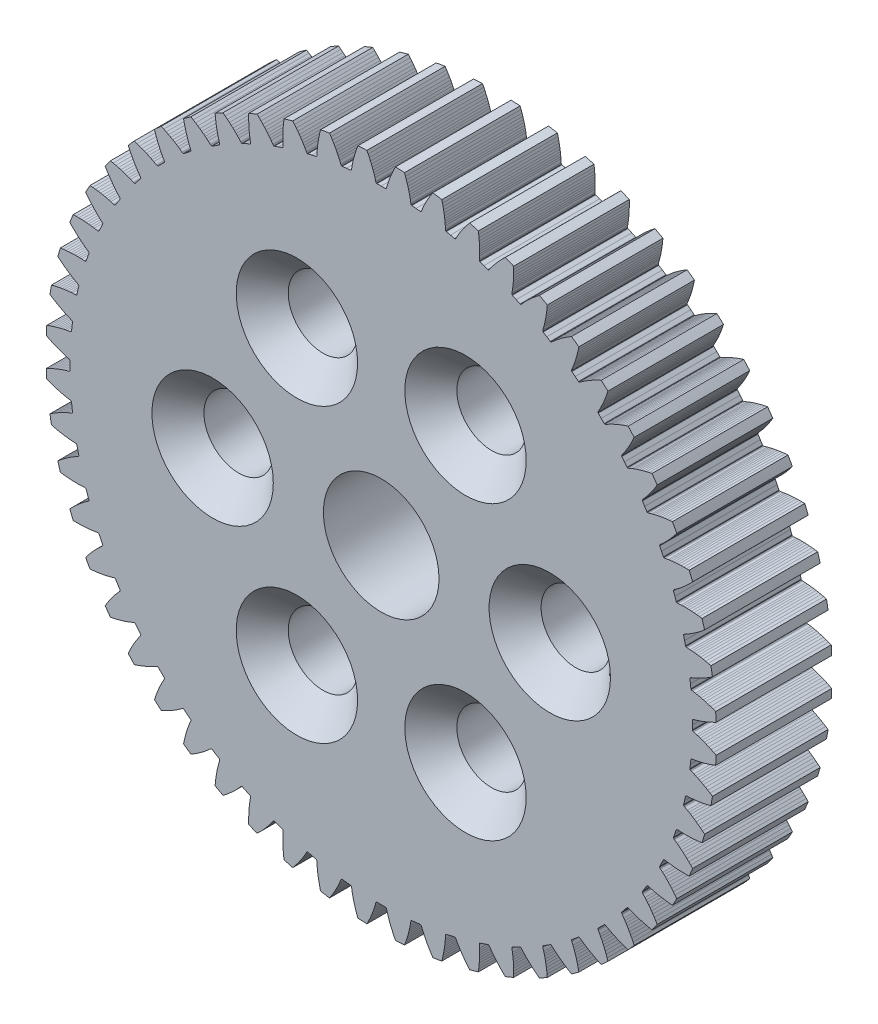
SolidWorks part; units mm, degrees
ref_plane "Front Plane" through (0, 0, 0) normal (0, 0, 1) x (1, 0, 0)
ref_plane "Top Plane" through (0, 0, 0) normal (0, 1, 0) x (1, 0, 0)
ref_plane "Right Plane" through (0, 0, 0) normal (1, 0, 0) x (0, 0, -1)
sketch "Model" plane through (0, 0, 0) normal (0, 0, 1) x (1, 0, 0)
  line L0 (3.6293, -2.6038) -> (3.7497, -2.5287)
  line L1 (3.7497, -2.5287) -> (3.8679, -2.4582)
  line L2 (3.8679, -2.4582) -> (3.9805, -2.3943)
  line L3 (3.9805, -2.3943) -> (4.0864, -2.3371)
  line L4 (4.0864, -2.3371) -> (4.1897, -2.284)
  line L5 (4.1897, -2.284) -> (4.2877, -2.2362)
  line L6 (4.2877, -2.2362) -> (4.3792, -2.194)
  line L7 (4.3792, -2.194) -> (4.4674, -2.1555)
  line L8 (4.4674, -2.1555) -> (4.6115, -2.0968)
  line L9 (4.6115, -2.0968) -> (4.6397, -2.0819)
  line L10 (4.6397, -2.0819) -> (4.6602, -2.0669)
  line L11 (4.6602, -2.0669) -> (4.6732, -2.0522)
  line L12 (4.6732, -2.0522) -> (4.6784, -2.0379)
  line L13 (4.6784, -2.0379) -> (4.6766, -2.0187)
  line L14 (4.6766, -2.0187) -> (4.6515, -1.8082)
  line L15 (4.6515, -1.8082) -> (4.6291, -1.5975)
  line L16 (4.6291, -1.5975) -> (4.6266, -1.5783)
  line L17 (4.6266, -1.5783) -> (4.6183, -1.5656)
  line L18 (4.6183, -1.5656) -> (4.6025, -1.5541)
  line L19 (4.6025, -1.5541) -> (4.5791, -1.5441)
  line L20 (4.5791, -1.5441) -> (4.5483, -1.5359)
  line L21 (4.5483, -1.5359) -> (4.3947, -1.5106)
  line L22 (4.3947, -1.5106) -> (4.3002, -1.4927)
  line L23 (4.3002, -1.4927) -> (4.2016, -1.4719)
  line L24 (4.2016, -1.4719) -> (4.0954, -1.4471)
  line L25 (4.0954, -1.4471) -> (3.9829, -1.4184)
  line L26 (3.9829, -1.4184) -> (3.8669, -1.3862)
  line L27 (3.8669, -1.3862) -> (3.7429, -1.3489)
  line L28 (3.7429, -1.3489) -> (3.612, -1.3065)
  line L29 (3.612, -1.3065) -> (3.4779, -1.26)
  line L30 (3.4779, -1.26) -> (3.3421, -1.2097)
  line L31 (3.3158, -0.7413) -> (3.4451, -0.6762)
  line L32 (3.4451, -0.6762) -> (3.5731, -0.6149)
  line L33 (3.5731, -0.6149) -> (3.6985, -0.5582)
  line L34 (3.6985, -0.5582) -> (3.8176, -0.5073)
  line L35 (3.8176, -0.5073) -> (3.9292, -0.4623)
  line L36 (3.9292, -0.4623) -> (4.0378, -0.4211)
  line L37 (4.0378, -0.4211) -> (4.1405, -0.3846)
  line L38 (4.1405, -0.3846) -> (4.2362, -0.3528)
  line L39 (4.2362, -0.3528) -> (4.3281, -0.3245)
  line L40 (4.3281, -0.3245) -> (4.4779, -0.2822)
  line L41 (4.4779, -0.2822) -> (4.5076, -0.2706)
  line L42 (4.5076, -0.2706) -> (4.5297, -0.258)
  line L43 (4.5297, -0.258) -> (4.5442, -0.2448)
  line L44 (4.5442, -0.2448) -> (4.551, -0.2313)
  line L45 (4.551, -0.2313) -> (4.5513, -0.2119)
  line L46 (4.5513, -0.2119) -> (4.55, 0)
  line L47 (4.55, 0) -> (4.5513, 0.2119)
  line L48 (4.5513, 0.2119) -> (4.551, 0.2313)
  line L49 (4.551, 0.2313) -> (4.5442, 0.2448)
  line L50 (4.5442, 0.2448) -> (4.5297, 0.258)
  line L51 (4.5297, 0.258) -> (4.5076, 0.2706)
  line L52 (4.5076, 0.2706) -> (4.4779, 0.2822)
  line L53 (4.4779, 0.2822) -> (4.3281, 0.3245)
  line L54 (4.3281, 0.3245) -> (4.2362, 0.3528)
  line L55 (4.2362, 0.3528) -> (4.1405, 0.3846)
  line L56 (4.1405, 0.3846) -> (4.0378, 0.4211)
  line L57 (4.0378, 0.4211) -> (3.9292, 0.4623)
  line L58 (3.9292, 0.4623) -> (3.8176, 0.5073)
  line L59 (3.8176, 0.5073) -> (3.6985, 0.5582)
  line L60 (3.6985, 0.5582) -> (3.5731, 0.6149)
  line L61 (3.5731, 0.6149) -> (3.4451, 0.6762)
  line L62 (3.4451, 0.6762) -> (3.3158, 0.7413)
  line L63 (3.3421, 1.2097) -> (3.4779, 1.26)
  line L64 (3.4779, 1.26) -> (3.612, 1.3065)
  line L65 (3.612, 1.3065) -> (3.7429, 1.3489)
  line L66 (3.7429, 1.3489) -> (3.8669, 1.3862)
  line L67 (3.8669, 1.3862) -> (3.9829, 1.4184)
  line L68 (3.9829, 1.4184) -> (4.0954, 1.4471)
  line L69 (4.0954, 1.4471) -> (4.2016, 1.4719)
  line L70 (4.2016, 1.4719) -> (4.3002, 1.4927)
  line L71 (4.3002, 1.4927) -> (4.3947, 1.5106)
  line L72 (4.3947, 1.5106) -> (4.5483, 1.5359)
  line L73 (4.5483, 1.5359) -> (4.5791, 1.5441)
  line L74 (4.5791, 1.5441) -> (4.6025, 1.5541)
  line L75 (4.6025, 1.5541) -> (4.6183, 1.5656)
  line L76 (4.6183, 1.5656) -> (4.6266, 1.5783)
  line L77 (4.6266, 1.5783) -> (4.6291, 1.5975)
  line L78 (4.6291, 1.5975) -> (4.6515, 1.8082)
  line L79 (4.6515, 1.8082) -> (4.6766, 2.0187)
  line L80 (4.6766, 2.0187) -> (4.6784, 2.0379)
  line L81 (4.6784, 2.0379) -> (4.6732, 2.0522)
  line L82 (4.6732, 2.0522) -> (4.6602, 2.0669)
  line L83 (4.6602, 2.0669) -> (4.6397, 2.0819)
  line L84 (4.6397, 2.0819) -> (4.6115, 2.0968)
  line L85 (4.6115, 2.0968) -> (4.4674, 2.1555)
  line L86 (4.4674, 2.1555) -> (4.3792, 2.194)
  line L87 (4.3792, 2.194) -> (4.2877, 2.2362)
  line L88 (4.2877, 2.2362) -> (4.1897, 2.284)
  line L89 (4.1897, 2.284) -> (4.0864, 2.3371)
  line L90 (4.0864, 2.3371) -> (3.9805, 2.3943)
  line L91 (3.9805, 2.3943) -> (3.8679, 2.4582)
  line L92 (3.8679, 2.4582) -> (3.7497, 2.5287)
  line L93 (3.7497, 2.5287) -> (3.6293, 2.6038)
  line L94 (3.6293, 2.6038) -> (3.5081, 2.6831)
  line L95 (3.5867, 3.1456) -> (3.7273, 3.1804)
  line L96 (3.7273, 3.1804) -> (3.8657, 3.2116)
  line L97 (3.8657, 3.2116) -> (4.0006, 3.239)
  line L98 (4.0006, 3.239) -> (4.128, 3.2621)
  line L99 (4.128, 3.2621) -> (4.2468, 3.2812)
  line L100 (4.2468, 3.2812) -> (4.3618, 3.2972)
  line L101 (4.3618, 3.2972) -> (4.4701, 3.3099)
  line L102 (4.4701, 3.3099) -> (4.5704, 3.3195)
  line L103 (4.5704, 3.3195) -> (4.6664, 3.3268)
  line L104 (4.6664, 3.3268) -> (4.8218, 3.3346)
  line L105 (4.8218, 3.3346) -> (4.8533, 3.3393)
  line L106 (4.8533, 3.3393) -> (4.8777, 3.3467)
  line L107 (4.8777, 3.3467) -> (4.8947, 3.3563)
  line L108 (4.8947, 3.3563) -> (4.9044, 3.368)
  line L109 (4.9044, 3.368) -> (4.9091, 3.3868)
  line L110 (4.9091, 3.3868) -> (4.9549, 3.5937)
  line L111 (4.9549, 3.5937) -> (5.0034, 3.8)
  line L112 (5.0034, 3.8) -> (5.0073, 3.8189)
  line L113 (5.0073, 3.8189) -> (5.0037, 3.8337)
  line L114 (5.0037, 3.8337) -> (4.9925, 3.8498)
  line L115 (4.9925, 3.8498) -> (4.9738, 3.867)
  line L116 (4.9738, 3.867) -> (4.9474, 3.8849)
  line L117 (4.9474, 3.8849) -> (4.8108, 3.9594)
  line L118 (4.8108, 3.9594) -> (4.7275, 4.0076)
  line L119 (4.7275, 4.0076) -> (4.6413, 4.0598)
  line L120 (4.6413, 4.0598) -> (4.5492, 4.1182)
  line L121 (4.5492, 4.1182) -> (4.4525, 4.1826)
  line L122 (4.4525, 4.1826) -> (4.3537, 4.2512)
  line L123 (4.3537, 4.2512) -> (4.249, 4.3274)
  line L124 (4.249, 4.3274) -> (4.1394, 4.4106)
  line L125 (4.1394, 4.4106) -> (4.0282, 4.4988)
  line L126 (4.0282, 4.4988) -> (3.9166, 4.5911)
  line L127 (4.0465, 5.0419) -> (4.1901, 5.0607)
  line L128 (4.1901, 5.0607) -> (4.3311, 5.0762)
  line L129 (4.3311, 5.0762) -> (4.4682, 5.0884)
  line L130 (4.4682, 5.0884) -> (4.5974, 5.0971)
  line L131 (4.5974, 5.0971) -> (4.7176, 5.1027)
  line L132 (4.7176, 5.1027) -> (4.8337, 5.1057)
  line L133 (4.8337, 5.1057) -> (4.9428, 5.1062)
  line L134 (4.9428, 5.1062) -> (5.0435, 5.1046)
  line L135 (5.0435, 5.1046) -> (5.1397, 5.101)
  line L136 (5.1397, 5.101) -> (5.295, 5.0915)
  line L137 (5.295, 5.0915) -> (5.3269, 5.0926)
  line L138 (5.3269, 5.0926) -> (5.3519, 5.0972)
  line L139 (5.3519, 5.0972) -> (5.3699, 5.1049)
  line L140 (5.3699, 5.1049) -> (5.3808, 5.1154)
  line L141 (5.3808, 5.1154) -> (5.3876, 5.1335)
  line L142 (5.3876, 5.1335) -> (5.4563, 5.334)
  line L143 (5.4563, 5.334) -> (5.5275, 5.5336)
  line L144 (5.5275, 5.5336) -> (5.5336, 5.552)
  line L145 (5.5336, 5.552) -> (5.5316, 5.567)
  line L146 (5.5316, 5.567) -> (5.5223, 5.5843)
  line L147 (5.5223, 5.5843) -> (5.5056, 5.6035)
  line L148 (5.5056, 5.6035) -> (5.4814, 5.6242)
  line L149 (5.4814, 5.6242) -> (5.354, 5.7136)
  line L150 (5.354, 5.7136) -> (5.2766, 5.7707)
  line L151 (5.2766, 5.7707) -> (5.1968, 5.8323)
  line L152 (5.1968, 5.8323) -> (5.1119, 5.9007)
  line L153 (5.1119, 5.9007) -> (5.023, 5.9754)
  line L154 (5.023, 5.9754) -> (4.9325, 6.0547)
  line L155 (4.9325, 6.0547) -> (4.8369, 6.1421)
  line L156 (4.8369, 6.1421) -> (4.7373, 6.2371)
  line L157 (4.7373, 6.2371) -> (4.6367, 6.3371)
  line L158 (4.6367, 6.3371) -> (4.5362, 6.4414)
  line L159 (4.7157, 6.8748) -> (4.8605, 6.8774)
  line L160 (4.8605, 6.8774) -> (5.0024, 6.877)
  line L161 (5.0024, 6.877) -> (5.14, 6.8738)
  line L162 (5.14, 6.8738) -> (5.2694, 6.868)
  line L163 (5.2694, 6.868) -> (5.3894, 6.8601)
  line L164 (5.3894, 6.8601) -> (5.5052, 6.8501)
  line L165 (5.5052, 6.8501) -> (5.6136, 6.8384)
  line L166 (5.6136, 6.8384) -> (5.7135, 6.8255)
  line L167 (5.7135, 6.8255) -> (5.8086, 6.8112)
  line L168 (5.8086, 6.8112) -> (5.9619, 6.7843)
  line L169 (5.9619, 6.7843) -> (5.9937, 6.7818)
  line L170 (5.9937, 6.7818) -> (6.0191, 6.7836)
  line L171 (6.0191, 6.7836) -> (6.0379, 6.7892)
  line L172 (6.0379, 6.7892) -> (6.0499, 6.7984)
  line L173 (6.0499, 6.7984) -> (6.0586, 6.8157)
  line L174 (6.0586, 6.8157) -> (6.1494, 7.0072)
  line L175 (6.1494, 7.0072) -> (6.2425, 7.1976)
  line L176 (6.2425, 7.1976) -> (6.2506, 7.2151)
  line L177 (6.2506, 7.2151) -> (6.2503, 7.2303)
  line L178 (6.2503, 7.2303) -> (6.243, 7.2485)
  line L179 (6.243, 7.2485) -> (6.2285, 7.2695)
  line L180 (6.2285, 7.2695) -> (6.2068, 7.2928)
  line L181 (6.2068, 7.2928) -> (6.0902, 7.3958)
  line L182 (6.0902, 7.3958) -> (6.0197, 7.4613)
  line L183 (6.0197, 7.4613) -> (5.9473, 7.5314)
  line L184 (5.9473, 7.5314) -> (5.8706, 7.6089)
  line L185 (5.8706, 7.6089) -> (5.7906, 7.6931)
  line L186 (5.7906, 7.6931) -> (5.7096, 7.782)
  line L187 (5.7096, 7.782) -> (5.6244, 7.8796)
  line L188 (5.6244, 7.8796) -> (5.536, 7.9851)
  line L189 (5.536, 7.9851) -> (5.4473, 8.0958)
  line L190 (5.4473, 8.0958) -> (5.359, 8.2106)
  line L191 (5.586, 8.6212) -> (5.7301, 8.6076)
  line L192 (5.7301, 8.6076) -> (5.8711, 8.5914)
  line L193 (5.8711, 8.5914) -> (6.0075, 8.5727)
  line L194 (6.0075, 8.5727) -> (6.1354, 8.5525)
  line L195 (6.1354, 8.5525) -> (6.2538, 8.5312)
  line L196 (6.2538, 8.5312) -> (6.3677, 8.5083)
  line L197 (6.3677, 8.5083) -> (6.4741, 8.4845)
  line L198 (6.4741, 8.4845) -> (6.5719, 8.4605)
  line L199 (6.5719, 8.4605) -> (6.6649, 8.4357)
  line L200 (6.6649, 8.4357) -> (6.8142, 8.3917)
  line L201 (6.8142, 8.3917) -> (6.8455, 8.3858)
  line L202 (6.8455, 8.3858) -> (6.8709, 8.3846)
  line L203 (6.8709, 8.3846) -> (6.8902, 8.3881)
  line L204 (6.8902, 8.3881) -> (6.9032, 8.396)
  line L205 (6.9032, 8.396) -> (6.9138, 8.4122)
  line L206 (6.9138, 8.4122) -> (7.0254, 8.5923)
  line L207 (7.0254, 8.5923) -> (7.1393, 8.771)
  line L208 (7.1393, 8.771) -> (7.1493, 8.7876)
  line L209 (7.1493, 8.7876) -> (7.1507, 8.8027)
  line L210 (7.1507, 8.8027) -> (7.1455, 8.8216)
  line L211 (7.1455, 8.8216) -> (7.1335, 8.844)
  line L212 (7.1335, 8.844) -> (7.1145, 8.8697)
  line L213 (7.1145, 8.8697) -> (7.0101, 8.9851)
  line L214 (7.0101, 8.9851) -> (6.9474, 9.0581)
  line L215 (6.9474, 9.0581) -> (6.8833, 9.1358)
  line L216 (6.8833, 9.1358) -> (6.8157, 9.2214)
  line L217 (6.8157, 9.2214) -> (6.7457, 9.314)
  line L218 (6.7457, 9.314) -> (6.6751, 9.4115)
  line L219 (6.6751, 9.4115) -> (6.6014, 9.5179)
  line L220 (6.6014, 9.5179) -> (6.5254, 9.6327)
  line L221 (6.5254, 9.6327) -> (6.4496, 9.7527)
  line L222 (6.4496, 9.7527) -> (6.3748, 9.8767)
  line L223 (6.6463, 10.2593) -> (6.788, 10.2296)
  line L224 (6.788, 10.2296) -> (6.9263, 10.1976)
  line L225 (6.9263, 10.1976) -> (7.0597, 10.1639)
  line L226 (7.0597, 10.1639) -> (7.1845, 10.1294)
  line L227 (7.1845, 10.1294) -> (7.2998, 10.095)
  line L228 (7.2998, 10.095) -> (7.4104, 10.0595)
  line L229 (7.4104, 10.0595) -> (7.5135, 10.024)
  line L230 (7.5135, 10.024) -> (7.608, 9.9892)
  line L231 (7.608, 9.9892) -> (7.6976, 9.954)
  line L232 (7.6976, 9.954) -> (7.8411, 9.8937)
  line L233 (7.8411, 9.8937) -> (7.8715, 9.8842)
  line L234 (7.8715, 9.8842) -> (7.8967, 9.8803)
  line L235 (7.8967, 9.8803) -> (7.9162, 9.8816)
  line L236 (7.9162, 9.8816) -> (7.93, 9.8879)
  line L237 (7.93, 9.8879) -> (7.9423, 9.9029)
  line L238 (7.9423, 9.9029) -> (8.0734, 10.0694)
  line L239 (8.0734, 10.0694) -> (8.2066, 10.2342)
  line L240 (8.2066, 10.2342) -> (8.2184, 10.2495)
  line L241 (8.2184, 10.2495) -> (8.2215, 10.2644)
  line L242 (8.2215, 10.2644) -> (8.2184, 10.2838)
  line L243 (8.2184, 10.2838) -> (8.209, 10.3074)
  line L244 (8.209, 10.3074) -> (8.193, 10.335)
  line L245 (8.193, 10.335) -> (8.1022, 10.4614)
  line L246 (8.1022, 10.4614) -> (8.048, 10.5409)
  line L247 (8.048, 10.5409) -> (7.9931, 10.6254)
  line L248 (7.9931, 10.6254) -> (7.9355, 10.718)
  line L249 (7.9355, 10.718) -> (7.8763, 10.8179)
  line L250 (7.8763, 10.8179) -> (7.8171, 10.9226)
  line L251 (7.8171, 10.9226) -> (7.7557, 11.0366)
  line L252 (7.7557, 11.0366) -> (7.6931, 11.1592)
  line L253 (7.6931, 11.1592) -> (7.6312, 11.2869)
  line L254 (7.6312, 11.2869) -> (7.5707, 11.4185)
  line L255 (7.8833, 11.7683) -> (8.0208, 11.7229)
  line L256 (8.0208, 11.7229) -> (8.1546, 11.6757)
  line L257 (8.1546, 11.6757) -> (8.2835, 11.6272)
  line L258 (8.2835, 11.6272) -> (8.4036, 11.579)
  line L259 (8.4036, 11.579) -> (8.5144, 11.5319)
  line L260 (8.5144, 11.5319) -> (8.6203, 11.4842)
  line L261 (8.6203, 11.4842) -> (8.7187, 11.4374)
  line L262 (8.7187, 11.4374) -> (8.8088, 11.3922)
  line L263 (8.8088, 11.3922) -> (8.8939, 11.3473)
  line L264 (8.8939, 11.3473) -> (9.0296, 11.2712)
  line L265 (9.0296, 11.2712) -> (9.0589, 11.2584)
  line L266 (9.0589, 11.2584) -> (9.0834, 11.2517)
  line L267 (9.0834, 11.2517) -> (9.103, 11.2508)
  line L268 (9.103, 11.2508) -> (9.1174, 11.2556)
  line L269 (9.1174, 11.2556) -> (9.1313, 11.269)
  line L270 (9.1313, 11.269) -> (9.2802, 11.4198)
  line L271 (9.2802, 11.4198) -> (9.431, 11.5687)
  line L272 (9.431, 11.5687) -> (9.4444, 11.5826)
  line L273 (9.4444, 11.5826) -> (9.4492, 11.597)
  line L274 (9.4492, 11.597) -> (9.4483, 11.6166)
  line L275 (9.4483, 11.6166) -> (9.4416, 11.6411)
  line L276 (9.4416, 11.6411) -> (9.4288, 11.6704)
  line L277 (9.4288, 11.6704) -> (9.3527, 11.8061)
  line L278 (9.3527, 11.8061) -> (9.3078, 11.8912)
  line L279 (9.3078, 11.8912) -> (9.2626, 11.9813)
  line L280 (9.2626, 11.9813) -> (9.2158, 12.0797)
  line L281 (9.2158, 12.0797) -> (9.1681, 12.1856)
  line L282 (9.1681, 12.1856) -> (9.121, 12.2964)
  line L283 (9.121, 12.2964) -> (9.0728, 12.4165)
  line L284 (9.0728, 12.4165) -> (9.0243, 12.5454)
  line L285 (9.0243, 12.5454) -> (8.9771, 12.6792)
  line L286 (8.9771, 12.6792) -> (8.9317, 12.8167)
  line L287 (9.2815, 13.1293) -> (9.4131, 13.0688)
  line L288 (9.4131, 13.0688) -> (9.5408, 13.0069)
  line L289 (9.5408, 13.0069) -> (9.6634, 12.9443)
  line L290 (9.6634, 12.9443) -> (9.7774, 12.8829)
  line L291 (9.7774, 12.8829) -> (9.8821, 12.8237)
  line L292 (9.8821, 12.8237) -> (9.982, 12.7645)
  line L293 (9.982, 12.7645) -> (10.0746, 12.7069)
  line L294 (10.0746, 12.7069) -> (10.1591, 12.652)
  line L295 (10.1591, 12.652) -> (10.2386, 12.5978)
  line L296 (10.2386, 12.5978) -> (10.365, 12.507)
  line L297 (10.365, 12.507) -> (10.3926, 12.491)
  line L298 (10.3926, 12.491) -> (10.4162, 12.4816)
  line L299 (10.4162, 12.4816) -> (10.4356, 12.4785)
  line L300 (10.4356, 12.4785) -> (10.4505, 12.4816)
  line L301 (10.4505, 12.4816) -> (10.4658, 12.4934)
  line L302 (10.4658, 12.4934) -> (10.6306, 12.6266)
  line L303 (10.6306, 12.6266) -> (10.7971, 12.7577)
  line L304 (10.7971, 12.7577) -> (10.8121, 12.77)
  line L305 (10.8121, 12.77) -> (10.8184, 12.7838)
  line L306 (10.8184, 12.7838) -> (10.8197, 12.8034)
  line L307 (10.8197, 12.8034) -> (10.8158, 12.8285)
  line L308 (10.8158, 12.8285) -> (10.8063, 12.8589)
  line L309 (10.8063, 12.8589) -> (10.746, 13.0024)
  line L310 (10.746, 13.0024) -> (10.7108, 13.092)
  line L311 (10.7108, 13.092) -> (10.676, 13.1865)
  line L312 (10.676, 13.1865) -> (10.6405, 13.2896)
  line L313 (10.6405, 13.2896) -> (10.605, 13.4002)
  line L314 (10.605, 13.4002) -> (10.5706, 13.5155)
  line L315 (10.5706, 13.5155) -> (10.5361, 13.6403)
  line L316 (10.5361, 13.6403) -> (10.5024, 13.7737)
  line L317 (10.5024, 13.7737) -> (10.4704, 13.912)
  line L318 (10.4704, 13.912) -> (10.4407, 14.0537)
  line L319 (10.8233, 14.3252) -> (10.9473, 14.2504)
  line L320 (10.9473, 14.2504) -> (11.0673, 14.1746)
  line L321 (11.0673, 14.1746) -> (11.1821, 14.0986)
  line L322 (11.1821, 14.0986) -> (11.2885, 14.0249)
  line L323 (11.2885, 14.0249) -> (11.386, 13.9543)
  line L324 (11.386, 13.9543) -> (11.4786, 13.8843)
  line L325 (11.4786, 13.8843) -> (11.5642, 13.8167)
  line L326 (11.5642, 13.8167) -> (11.6419, 13.7526)
  line L327 (11.6419, 13.7526) -> (11.7149, 13.6899)
  line L328 (11.7149, 13.6899) -> (11.8303, 13.5855)
  line L329 (11.8303, 13.5855) -> (11.856, 13.5665)
  line L330 (11.856, 13.5665) -> (11.8784, 13.5545)
  line L331 (11.8784, 13.5545) -> (11.8973, 13.5493)
  line L332 (11.8973, 13.5493) -> (11.9124, 13.5507)
  line L333 (11.9124, 13.5507) -> (11.929, 13.5607)
  line L334 (11.929, 13.5607) -> (12.1077, 13.6746)
  line L335 (12.1077, 13.6746) -> (12.2878, 13.7862)
  line L336 (12.2878, 13.7862) -> (12.304, 13.7968)
  line L337 (12.304, 13.7968) -> (12.3119, 13.8098)
  line L338 (12.3119, 13.8098) -> (12.3154, 13.8291)
  line L339 (12.3154, 13.8291) -> (12.3142, 13.8545)
  line L340 (12.3142, 13.8545) -> (12.3083, 13.8858)
  line L341 (12.3083, 13.8858) -> (12.2644, 14.0351)
  line L342 (12.2644, 14.0351) -> (12.2395, 14.1281)
  line L343 (12.2395, 14.1281) -> (12.2155, 14.2259)
  line L344 (12.2155, 14.2259) -> (12.1917, 14.3323)
  line L345 (12.1917, 14.3323) -> (12.1688, 14.4462)
  line L346 (12.1688, 14.4462) -> (12.1475, 14.5646)
  line L347 (12.1475, 14.5646) -> (12.1273, 14.6925)
  line L348 (12.1273, 14.6925) -> (12.1086, 14.8289)
  line L349 (12.1086, 14.8289) -> (12.0924, 14.9699)
  line L350 (12.0924, 14.9699) -> (12.0788, 15.114)
  line L351 (12.4894, 15.341) -> (12.6042, 15.2527)
  line L352 (12.6042, 15.2527) -> (12.7149, 15.164)
  line L353 (12.7149, 15.164) -> (12.8204, 15.0756)
  line L354 (12.8204, 15.0756) -> (12.918, 14.9904)
  line L355 (12.918, 14.9904) -> (13.0069, 14.9094)
  line L356 (13.0069, 14.9094) -> (13.0911, 14.8294)
  line L357 (13.0911, 14.8294) -> (13.1686, 14.7527)
  line L358 (13.1686, 14.7527) -> (13.2387, 14.6803)
  line L359 (13.2387, 14.6803) -> (13.3042, 14.6098)
  line L360 (13.3042, 14.6098) -> (13.4072, 14.4932)
  line L361 (13.4072, 14.4932) -> (13.4305, 14.4715)
  line L362 (13.4305, 14.4715) -> (13.4515, 14.457)
  line L363 (13.4515, 14.457) -> (13.4697, 14.4497)
  line L364 (13.4697, 14.4497) -> (13.4849, 14.4494)
  line L365 (13.4849, 14.4494) -> (13.5024, 14.4575)
  line L366 (13.5024, 14.4575) -> (13.6928, 14.5506)
  line L367 (13.6928, 14.5506) -> (13.8843, 14.6414)
  line L368 (13.8843, 14.6414) -> (13.9016, 14.6501)
  line L369 (13.9016, 14.6501) -> (13.9108, 14.6621)
  line L370 (13.9108, 14.6621) -> (13.9164, 14.6809)
  line L371 (13.9164, 14.6809) -> (13.9182, 14.7063)
  line L372 (13.9182, 14.7063) -> (13.9157, 14.7381)
  line L373 (13.9157, 14.7381) -> (13.8888, 14.8914)
  line L374 (13.8888, 14.8914) -> (13.8745, 14.9865)
  line L375 (13.8745, 14.9865) -> (13.8616, 15.0864)
  line L376 (13.8616, 15.0864) -> (13.8499, 15.1948)
  line L377 (13.8499, 15.1948) -> (13.8399, 15.3106)
  line L378 (13.8399, 15.3106) -> (13.832, 15.4306)
  line L379 (13.832, 15.4306) -> (13.8262, 15.56)
  line L380 (13.8262, 15.56) -> (13.823, 15.6976)
  line L381 (13.823, 15.6976) -> (13.8226, 15.8395)
  line L382 (13.8226, 15.8395) -> (13.8252, 15.9843)
  line L383 (14.2586, 16.1638) -> (14.3629, 16.0633)
  line L384 (14.3629, 16.0633) -> (14.4629, 15.9627)
  line L385 (14.4629, 15.9627) -> (14.5579, 15.8631)
  line L386 (14.5579, 15.8631) -> (14.6453, 15.7675)
  line L387 (14.6453, 15.7675) -> (14.7246, 15.677)
  line L388 (14.7246, 15.677) -> (14.7993, 15.5881)
  line L389 (14.7993, 15.5881) -> (14.8677, 15.5032)
  line L390 (14.8677, 15.5032) -> (14.9293, 15.4234)
  line L391 (14.9293, 15.4234) -> (14.9864, 15.346)
  line L392 (14.9864, 15.346) -> (15.0758, 15.2186)
  line L393 (15.0758, 15.2186) -> (15.0965, 15.1944)
  line L394 (15.0965, 15.1944) -> (15.1157, 15.1777)
  line L395 (15.1157, 15.1777) -> (15.133, 15.1684)
  line L396 (15.133, 15.1684) -> (15.148, 15.1664)
  line L397 (15.148, 15.1664) -> (15.1664, 15.1725)
  line L398 (15.1664, 15.1725) -> (15.366, 15.2437)
  line L399 (15.366, 15.2437) -> (15.5665, 15.3124)
  line L400 (15.5665, 15.3124) -> (15.5846, 15.3192)
  line L401 (15.5846, 15.3192) -> (15.5951, 15.3301)
  line L402 (15.5951, 15.3301) -> (15.6028, 15.3481)
  line L403 (15.6028, 15.3481) -> (15.6074, 15.3731)
  line L404 (15.6074, 15.3731) -> (15.6085, 15.405)
  line L405 (15.6085, 15.405) -> (15.599, 15.5603)
  line L406 (15.599, 15.5603) -> (15.5954, 15.6565)
  line L407 (15.5954, 15.6565) -> (15.5938, 15.7572)
  line L408 (15.5938, 15.7572) -> (15.5943, 15.8663)
  line L409 (15.5943, 15.8663) -> (15.5973, 15.9824)
  line L410 (15.5973, 15.9824) -> (15.6029, 16.1026)
  line L411 (15.6029, 16.1026) -> (15.6116, 16.2318)
  line L412 (15.6116, 16.2318) -> (15.6238, 16.3689)
  line L413 (15.6238, 16.3689) -> (15.6393, 16.5099)
  line L414 (15.6393, 16.5099) -> (15.6581, 16.6535)
  line L415 (16.1089, 16.7834) -> (16.2012, 16.6718)
  line L416 (16.2012, 16.6718) -> (16.2894, 16.5606)
  line L417 (16.2894, 16.5606) -> (16.3726, 16.451)
  line L418 (16.3726, 16.451) -> (16.4488, 16.3463)
  line L419 (16.4488, 16.3463) -> (16.5175, 16.2475)
  line L420 (16.5175, 16.2475) -> (16.5818, 16.1508)
  line L421 (16.5818, 16.1508) -> (16.6402, 16.0587)
  line L422 (16.6402, 16.0587) -> (16.6924, 15.9726)
  line L423 (16.6924, 15.9726) -> (16.7406, 15.8892)
  line L424 (16.7406, 15.8892) -> (16.8151, 15.7526)
  line L425 (16.8151, 15.7526) -> (16.833, 15.7262)
  line L426 (16.833, 15.7262) -> (16.8502, 15.7075)
  line L427 (16.8502, 15.7075) -> (16.8663, 15.6963)
  line L428 (16.8663, 15.6963) -> (16.8811, 15.6927)
  line L429 (16.8811, 15.6927) -> (16.9, 15.6966)
  line L430 (16.9, 15.6966) -> (17.1063, 15.7451)
  line L431 (17.1063, 15.7451) -> (17.3132, 15.7909)
  line L432 (17.3132, 15.7909) -> (17.332, 15.7956)
  line L433 (17.332, 15.7956) -> (17.3437, 15.8053)
  line L434 (17.3437, 15.8053) -> (17.3533, 15.8223)
  line L435 (17.3533, 15.8223) -> (17.3607, 15.8467)
  line L436 (17.3607, 15.8467) -> (17.3654, 15.8782)
  line L437 (17.3654, 15.8782) -> (17.3732, 16.0336)
  line L438 (17.3732, 16.0336) -> (17.3805, 16.1296)
  line L439 (17.3805, 16.1296) -> (17.3901, 16.2299)
  line L440 (17.3901, 16.2299) -> (17.4029, 16.3382)
  line L441 (17.4029, 16.3382) -> (17.4188, 16.4532)
  line L442 (17.4188, 16.4532) -> (17.4379, 16.572)
  line L443 (17.4379, 16.572) -> (17.461, 16.6994)
  line L444 (17.461, 16.6994) -> (17.4884, 16.8343)
  line L445 (17.4884, 16.8343) -> (17.5196, 16.9727)
  line L446 (17.5196, 16.9727) -> (17.5544, 17.1133)
  line L447 (18.0169, 17.1919) -> (18.0962, 17.0707)
  line L448 (18.0962, 17.0707) -> (18.1713, 16.9503)
  line L449 (18.1713, 16.9503) -> (18.2418, 16.8321)
  line L450 (18.2418, 16.8321) -> (18.3057, 16.7195)
  line L451 (18.3057, 16.7195) -> (18.3629, 16.6136)
  line L452 (18.3629, 16.6136) -> (18.416, 16.5103)
  line L453 (18.416, 16.5103) -> (18.4638, 16.4123)
  line L454 (18.4638, 16.4123) -> (18.506, 16.3208)
  line L455 (18.506, 16.3208) -> (18.5445, 16.2326)
  line L456 (18.5445, 16.2326) -> (18.6033, 16.0885)
  line L457 (18.6033, 16.0885) -> (18.6181, 16.0603)
  line L458 (18.6181, 16.0603) -> (18.6331, 16.0398)
  line L459 (18.6331, 16.0398) -> (18.6478, 16.0268)
  line L460 (18.6478, 16.0268) -> (18.6621, 16.0216)
  line L461 (18.6621, 16.0216) -> (18.6813, 16.0234)
  line L462 (18.6813, 16.0234) -> (18.8918, 16.0485)
  line L463 (18.8918, 16.0485) -> (19.1025, 16.0709)
  line L464 (19.1025, 16.0709) -> (19.1217, 16.0734)
  line L465 (19.1217, 16.0734) -> (19.1344, 16.0817)
  line L466 (19.1344, 16.0817) -> (19.1459, 16.0975)
  line L467 (19.1459, 16.0975) -> (19.1559, 16.1209)
  line L468 (19.1559, 16.1209) -> (19.1641, 16.1517)
  line L469 (19.1641, 16.1517) -> (19.1894, 16.3053)
  line L470 (19.1894, 16.3053) -> (19.2073, 16.3998)
  line L471 (19.2073, 16.3998) -> (19.2281, 16.4984)
  line L472 (19.2281, 16.4984) -> (19.2529, 16.6046)
  line L473 (19.2529, 16.6046) -> (19.2816, 16.7171)
  line L474 (19.2816, 16.7171) -> (19.3138, 16.8331)
  line L475 (19.3138, 16.8331) -> (19.3511, 16.9571)
  line L476 (19.3511, 16.9571) -> (19.3935, 17.088)
  line L477 (19.3935, 17.088) -> (19.44, 17.2221)
  line L478 (19.44, 17.2221) -> (19.4903, 17.3579)
  line L479 (19.9587, 17.3842) -> (20.0238, 17.2549)
  line L480 (20.0238, 17.2549) -> (20.0851, 17.1269)
  line L481 (20.0851, 17.1269) -> (20.1418, 17.0015)
  line L482 (20.1418, 17.0015) -> (20.1927, 16.8824)
  line L483 (20.1927, 16.8824) -> (20.2377, 16.7708)
  line L484 (20.2377, 16.7708) -> (20.2789, 16.6622)
  line L485 (20.2789, 16.6622) -> (20.3154, 16.5595)
  line L486 (20.3154, 16.5595) -> (20.3472, 16.4639)
  line L487 (20.3472, 16.4639) -> (20.3755, 16.3719)
  line L488 (20.3755, 16.3719) -> (20.4178, 16.2222)
  line L489 (20.4178, 16.2222) -> (20.4294, 16.1924)
  line L490 (20.4294, 16.1924) -> (20.442, 16.1703)
  line L491 (20.442, 16.1703) -> (20.4552, 16.1558)
  line L492 (20.4552, 16.1558) -> (20.4688, 16.149)
  line L493 (20.4688, 16.149) -> (20.4881, 16.1487)
  line L494 (20.4881, 16.1487) -> (20.7, 16.15)
  line L495 (20.7, 16.15) -> (20.9119, 16.1487)
  line L496 (20.9119, 16.1487) -> (20.9313, 16.149)
  line L497 (20.9313, 16.149) -> (20.9448, 16.1558)
  line L498 (20.9448, 16.1558) -> (20.958, 16.1703)
  line L499 (20.958, 16.1703) -> (20.9706, 16.1924)
  line L500 (20.9706, 16.1924) -> (20.9822, 16.2222)
  line L501 (20.9822, 16.2222) -> (21.0245, 16.3719)
  line L502 (21.0245, 16.3719) -> (21.0529, 16.4639)
  line L503 (21.0529, 16.4639) -> (21.0846, 16.5595)
  line L504 (21.0846, 16.5595) -> (21.1211, 16.6622)
  line L505 (21.1211, 16.6622) -> (21.1623, 16.7708)
  line L506 (21.1623, 16.7708) -> (21.2073, 16.8824)
  line L507 (21.2073, 16.8824) -> (21.2582, 17.0015)
  line L508 (21.2582, 17.0015) -> (21.3149, 17.1269)
  line L509 (21.3149, 17.1269) -> (21.3762, 17.2549)
  line L510 (21.3762, 17.2549) -> (21.4413, 17.3842)
  line L511 (21.9097, 17.3579) -> (21.96, 17.2221)
  line L512 (21.96, 17.2221) -> (22.0065, 17.088)
  line L513 (22.0065, 17.088) -> (22.0489, 16.9571)
  line L514 (22.0489, 16.9571) -> (22.0862, 16.8331)
  line L515 (22.0862, 16.8331) -> (22.1184, 16.7171)
  line L516 (22.1184, 16.7171) -> (22.1471, 16.6046)
  line L517 (22.1471, 16.6046) -> (22.1719, 16.4984)
  line L518 (22.1719, 16.4984) -> (22.1927, 16.3998)
  line L519 (22.1927, 16.3998) -> (22.2106, 16.3053)
  line L520 (22.2106, 16.3053) -> (22.2359, 16.1517)
  line L521 (22.2359, 16.1517) -> (22.2441, 16.1209)
  line L522 (22.2441, 16.1209) -> (22.2541, 16.0975)
  line L523 (22.2541, 16.0975) -> (22.2656, 16.0817)
  line L524 (22.2656, 16.0817) -> (22.2783, 16.0734)
  line L525 (22.2783, 16.0734) -> (22.2975, 16.0709)
  line L526 (22.2975, 16.0709) -> (22.5082, 16.0485)
  line L527 (22.5082, 16.0485) -> (22.7187, 16.0234)
  line L528 (22.7187, 16.0234) -> (22.7379, 16.0216)
  line L529 (22.7379, 16.0216) -> (22.7522, 16.0268)
  line L530 (22.7522, 16.0268) -> (22.7669, 16.0398)
  line L531 (22.7669, 16.0398) -> (22.7819, 16.0603)
  line L532 (22.7819, 16.0603) -> (22.7968, 16.0885)
  line L533 (22.7968, 16.0885) -> (22.8555, 16.2326)
  line L534 (22.8555, 16.2326) -> (22.894, 16.3208)
  line L535 (22.894, 16.3208) -> (22.9362, 16.4123)
  line L536 (22.9362, 16.4123) -> (22.984, 16.5103)
  line L537 (22.984, 16.5103) -> (23.0371, 16.6136)
  line L538 (23.0371, 16.6136) -> (23.0943, 16.7195)
  line L539 (23.0943, 16.7195) -> (23.1582, 16.8321)
  line L540 (23.1582, 16.8321) -> (23.2287, 16.9503)
  line L541 (23.2287, 16.9503) -> (23.3038, 17.0707)
  line L542 (23.3038, 17.0707) -> (23.3831, 17.1919)
  line L543 (23.8456, 17.1133) -> (23.8804, 16.9727)
  line L544 (23.8804, 16.9727) -> (23.9116, 16.8343)
  line L545 (23.9116, 16.8343) -> (23.939, 16.6994)
  line L546 (23.939, 16.6994) -> (23.9622, 16.572)
  line L547 (23.9622, 16.572) -> (23.9812, 16.4532)
  line L548 (23.9812, 16.4532) -> (23.9972, 16.3382)
  line L549 (23.9972, 16.3382) -> (24.0099, 16.2299)
  line L550 (24.0099, 16.2299) -> (24.0195, 16.1296)
  line L551 (24.0195, 16.1296) -> (24.0268, 16.0336)
  line L552 (24.0268, 16.0336) -> (24.0346, 15.8782)
  line L553 (24.0346, 15.8782) -> (24.0393, 15.8467)
  line L554 (24.0393, 15.8467) -> (24.0467, 15.8223)
  line L555 (24.0467, 15.8223) -> (24.0563, 15.8053)
  line L556 (24.0563, 15.8053) -> (24.068, 15.7956)
  line L557 (24.068, 15.7956) -> (24.0868, 15.7909)
  line L558 (24.0868, 15.7909) -> (24.2937, 15.7451)
  line L559 (24.2937, 15.7451) -> (24.5, 15.6966)
  line L560 (24.5, 15.6966) -> (24.5189, 15.6927)
  line L561 (24.5189, 15.6927) -> (24.5337, 15.6963)
  line L562 (24.5337, 15.6963) -> (24.5498, 15.7075)
  line L563 (24.5498, 15.7075) -> (24.567, 15.7262)
  line L564 (24.567, 15.7262) -> (24.5849, 15.7526)
  line L565 (24.5849, 15.7526) -> (24.6594, 15.8892)
  line L566 (24.6594, 15.8892) -> (24.7076, 15.9726)
  line L567 (24.7076, 15.9726) -> (24.7598, 16.0587)
  line L568 (24.7598, 16.0587) -> (24.8182, 16.1508)
  line L569 (24.8182, 16.1508) -> (24.8826, 16.2475)
  line L570 (24.8826, 16.2475) -> (24.9512, 16.3463)
  line L571 (24.9512, 16.3463) -> (25.0274, 16.451)
  line L572 (25.0274, 16.451) -> (25.1106, 16.5606)
  line L573 (25.1106, 16.5606) -> (25.1988, 16.6718)
  line L574 (25.1988, 16.6718) -> (25.2911, 16.7834)
  line L575 (25.7419, 16.6535) -> (25.7607, 16.5099)
  line L576 (25.7607, 16.5099) -> (25.7762, 16.3689)
  line L577 (25.7762, 16.3689) -> (25.7884, 16.2318)
  line L578 (25.7884, 16.2318) -> (25.7971, 16.1026)
  line L579 (25.7971, 16.1026) -> (25.8027, 15.9824)
  line L580 (25.8027, 15.9824) -> (25.8057, 15.8663)
  line L581 (25.8057, 15.8663) -> (25.8062, 15.7572)
  line L582 (25.8062, 15.7572) -> (25.8046, 15.6565)
  line L583 (25.8046, 15.6565) -> (25.801, 15.5603)
  line L584 (25.801, 15.5603) -> (25.7915, 15.405)
  line L585 (25.7915, 15.405) -> (25.7926, 15.3731)
  line L586 (25.7926, 15.3731) -> (25.7972, 15.3481)
  line L587 (25.7972, 15.3481) -> (25.8049, 15.3301)
  line L588 (25.8049, 15.3301) -> (25.8154, 15.3192)
  line L589 (25.8154, 15.3192) -> (25.8335, 15.3124)
  line L590 (25.8335, 15.3124) -> (26.034, 15.2437)
  line L591 (26.034, 15.2437) -> (26.2336, 15.1725)
  line L592 (26.2336, 15.1725) -> (26.252, 15.1664)
  line L593 (26.252, 15.1664) -> (26.267, 15.1684)
  line L594 (26.267, 15.1684) -> (26.2843, 15.1777)
  line L595 (26.2843, 15.1777) -> (26.3035, 15.1944)
  line L596 (26.3035, 15.1944) -> (26.3242, 15.2186)
  line L597 (26.3242, 15.2186) -> (26.4136, 15.346)
  line L598 (26.4136, 15.346) -> (26.4707, 15.4234)
  line L599 (26.4707, 15.4234) -> (26.5323, 15.5032)
  line L600 (26.5323, 15.5032) -> (26.6007, 15.5881)
  line L601 (26.6007, 15.5881) -> (26.6754, 15.677)
  line L602 (26.6754, 15.677) -> (26.7547, 15.7675)
  line L603 (26.7547, 15.7675) -> (26.8421, 15.8631)
  line L604 (26.8421, 15.8631) -> (26.9371, 15.9627)
  line L605 (26.9371, 15.9627) -> (27.0371, 16.0633)
  line L606 (27.0371, 16.0633) -> (27.1414, 16.1638)
  line L607 (27.5748, 15.9843) -> (27.5774, 15.8395)
  line L608 (27.5774, 15.8395) -> (27.577, 15.6976)
  line L609 (27.577, 15.6976) -> (27.5738, 15.56)
  line L610 (27.5738, 15.56) -> (27.568, 15.4306)
  line L611 (27.568, 15.4306) -> (27.5601, 15.3106)
  line L612 (27.5601, 15.3106) -> (27.5501, 15.1948)
  line L613 (27.5501, 15.1948) -> (27.5384, 15.0864)
  line L614 (27.5384, 15.0864) -> (27.5255, 14.9865)
  line L615 (27.5255, 14.9865) -> (27.5112, 14.8914)
  line L616 (27.5112, 14.8914) -> (27.4843, 14.7381)
  line L617 (27.4843, 14.7381) -> (27.4818, 14.7063)
  line L618 (27.4818, 14.7063) -> (27.4836, 14.6809)
  line L619 (27.4836, 14.6809) -> (27.4892, 14.6621)
  line L620 (27.4892, 14.6621) -> (27.4984, 14.6501)
  line L621 (27.4984, 14.6501) -> (27.5157, 14.6414)
  line L622 (27.5157, 14.6414) -> (27.7072, 14.5506)
  line L623 (27.7072, 14.5506) -> (27.8976, 14.4575)
  line L624 (27.8976, 14.4575) -> (27.9151, 14.4494)
  line L625 (27.9151, 14.4494) -> (27.9303, 14.4497)
  line L626 (27.9303, 14.4497) -> (27.9485, 14.457)
  line L627 (27.9485, 14.457) -> (27.9695, 14.4715)
  line L628 (27.9695, 14.4715) -> (27.9928, 14.4932)
  line L629 (27.9928, 14.4932) -> (28.0958, 14.6098)
  line L630 (28.0958, 14.6098) -> (28.1613, 14.6803)
  line L631 (28.1613, 14.6803) -> (28.2314, 14.7527)
  line L632 (28.2314, 14.7527) -> (28.3089, 14.8294)
  line L633 (28.3089, 14.8294) -> (28.3931, 14.9094)
  line L634 (28.3931, 14.9094) -> (28.482, 14.9904)
  line L635 (28.482, 14.9904) -> (28.5796, 15.0756)
  line L636 (28.5796, 15.0756) -> (28.6851, 15.164)
  line L637 (28.6851, 15.164) -> (28.7958, 15.2527)
  line L638 (28.7958, 15.2527) -> (28.9106, 15.341)
  line L639 (29.3212, 15.114) -> (29.3076, 14.9699)
  line L640 (29.3076, 14.9699) -> (29.2914, 14.8289)
  line L641 (29.2914, 14.8289) -> (29.2727, 14.6925)
  line L642 (29.2727, 14.6925) -> (29.2525, 14.5646)
  line L643 (29.2525, 14.5646) -> (29.2312, 14.4462)
  line L644 (29.2312, 14.4462) -> (29.2083, 14.3323)
  line L645 (29.2083, 14.3323) -> (29.1845, 14.2259)
  line L646 (29.1845, 14.2259) -> (29.1605, 14.1281)
  line L647 (29.1605, 14.1281) -> (29.1357, 14.0351)
  line L648 (29.1357, 14.0351) -> (29.0917, 13.8858)
  line L649 (29.0917, 13.8858) -> (29.0858, 13.8545)
  line L650 (29.0858, 13.8545) -> (29.0846, 13.8291)
  line L651 (29.0846, 13.8291) -> (29.0881, 13.8098)
  line L652 (29.0881, 13.8098) -> (29.096, 13.7968)
  line L653 (29.096, 13.7968) -> (29.1122, 13.7862)
  line L654 (29.1122, 13.7862) -> (29.2923, 13.6746)
  line L655 (29.2923, 13.6746) -> (29.471, 13.5607)
  line L656 (29.471, 13.5607) -> (29.4876, 13.5507)
  line L657 (29.4876, 13.5507) -> (29.5027, 13.5493)
  line L658 (29.5027, 13.5493) -> (29.5216, 13.5545)
  line L659 (29.5216, 13.5545) -> (29.544, 13.5665)
  line L660 (29.544, 13.5665) -> (29.5697, 13.5855)
  line L661 (29.5697, 13.5855) -> (29.6851, 13.6899)
  line L662 (29.6851, 13.6899) -> (29.7581, 13.7526)
  line L663 (29.7581, 13.7526) -> (29.8358, 13.8167)
  line L664 (29.8358, 13.8167) -> (29.9214, 13.8843)
  line L665 (29.9214, 13.8843) -> (30.014, 13.9543)
  line L666 (30.014, 13.9543) -> (30.1115, 14.0249)
  line L667 (30.1115, 14.0249) -> (30.2179, 14.0986)
  line L668 (30.2179, 14.0986) -> (30.3327, 14.1746)
  line L669 (30.3327, 14.1746) -> (30.4527, 14.2504)
  line L670 (30.4527, 14.2504) -> (30.5767, 14.3252)
  line L671 (30.9593, 14.0537) -> (30.9296, 13.912)
  line L672 (30.9296, 13.912) -> (30.8977, 13.7737)
  line L673 (30.8977, 13.7737) -> (30.8639, 13.6403)
  line L674 (30.8639, 13.6403) -> (30.8294, 13.5155)
  line L675 (30.8294, 13.5155) -> (30.795, 13.4002)
  line L676 (30.795, 13.4002) -> (30.7595, 13.2896)
  line L677 (30.7595, 13.2896) -> (30.724, 13.1865)
  line L678 (30.724, 13.1865) -> (30.6892, 13.092)
  line L679 (30.6892, 13.092) -> (30.654, 13.0024)
  line L680 (30.654, 13.0024) -> (30.5937, 12.8589)
  line L681 (30.5937, 12.8589) -> (30.5842, 12.8285)
  line L682 (30.5842, 12.8285) -> (30.5803, 12.8034)
  line L683 (30.5803, 12.8034) -> (30.5816, 12.7838)
  line L684 (30.5816, 12.7838) -> (30.5879, 12.77)
  line L685 (30.5879, 12.77) -> (30.6029, 12.7577)
  line L686 (30.6029, 12.7577) -> (30.7694, 12.6266)
  line L687 (30.7694, 12.6266) -> (30.9342, 12.4934)
  line L688 (30.9342, 12.4934) -> (30.9495, 12.4816)
  line L689 (30.9495, 12.4816) -> (30.9644, 12.4785)
  line L690 (30.9644, 12.4785) -> (30.9838, 12.4816)
  line L691 (30.9838, 12.4816) -> (31.0074, 12.491)
  line L692 (31.0074, 12.491) -> (31.035, 12.507)
  line L693 (31.035, 12.507) -> (31.1614, 12.5978)
  line L694 (31.1614, 12.5978) -> (31.2409, 12.652)
  line L695 (31.2409, 12.652) -> (31.3254, 12.7069)
  line L696 (31.3254, 12.7069) -> (31.418, 12.7645)
  line L697 (31.418, 12.7645) -> (31.5179, 12.8237)
  line L698 (31.5179, 12.8237) -> (31.6226, 12.8829)
  line L699 (31.6226, 12.8829) -> (31.7366, 12.9443)
  line L700 (31.7366, 12.9443) -> (31.8592, 13.0069)
  line L701 (31.8592, 13.0069) -> (31.9869, 13.0688)
  line L702 (31.9869, 13.0688) -> (32.1185, 13.1293)
  line L703 (32.4683, 12.8167) -> (32.4229, 12.6792)
  line L704 (32.4229, 12.6792) -> (32.3757, 12.5454)
  line L705 (32.3757, 12.5454) -> (32.3272, 12.4165)
  line L706 (32.3272, 12.4165) -> (32.279, 12.2964)
  line L707 (32.279, 12.2964) -> (32.2319, 12.1856)
  line L708 (32.2319, 12.1856) -> (32.1842, 12.0797)
  line L709 (32.1842, 12.0797) -> (32.1374, 11.9813)
  line L710 (32.1374, 11.9813) -> (32.0922, 11.8912)
  line L711 (32.0922, 11.8912) -> (32.0473, 11.8061)
  line L712 (32.0473, 11.8061) -> (31.9712, 11.6704)
  line L713 (31.9712, 11.6704) -> (31.9584, 11.6411)
  line L714 (31.9584, 11.6411) -> (31.9517, 11.6166)
  line L715 (31.9517, 11.6166) -> (31.9508, 11.597)
  line L716 (31.9508, 11.597) -> (31.9556, 11.5826)
  line L717 (31.9556, 11.5826) -> (31.969, 11.5687)
  line L718 (31.969, 11.5687) -> (32.1198, 11.4198)
  line L719 (32.1198, 11.4198) -> (32.2687, 11.269)
  line L720 (32.2687, 11.269) -> (32.2826, 11.2556)
  line L721 (32.2826, 11.2556) -> (32.297, 11.2508)
  line L722 (32.297, 11.2508) -> (32.3166, 11.2517)
  line L723 (32.3166, 11.2517) -> (32.3411, 11.2584)
  line L724 (32.3411, 11.2584) -> (32.3704, 11.2712)
  line L725 (32.3704, 11.2712) -> (32.5061, 11.3473)
  line L726 (32.5061, 11.3473) -> (32.5912, 11.3922)
  line L727 (32.5912, 11.3922) -> (32.6813, 11.4374)
  line L728 (32.6813, 11.4374) -> (32.7797, 11.4842)
  line L729 (32.7797, 11.4842) -> (32.8856, 11.5319)
  line L730 (32.8856, 11.5319) -> (32.9964, 11.579)
  line L731 (32.9964, 11.579) -> (33.1165, 11.6272)
  line L732 (33.1165, 11.6272) -> (33.2454, 11.6757)
  line L733 (33.2454, 11.6757) -> (33.3792, 11.7229)
  line L734 (33.3792, 11.7229) -> (33.5167, 11.7683)
  line L735 (33.8293, 11.4185) -> (33.7688, 11.2869)
  line L736 (33.7688, 11.2869) -> (33.7069, 11.1592)
  line L737 (33.7069, 11.1592) -> (33.6443, 11.0366)
  line L738 (33.6443, 11.0366) -> (33.5829, 10.9226)
  line L739 (33.5829, 10.9226) -> (33.5237, 10.8179)
  line L740 (33.5237, 10.8179) -> (33.4645, 10.718)
  line L741 (33.4645, 10.718) -> (33.4069, 10.6254)
  line L742 (33.4069, 10.6254) -> (33.352, 10.5409)
  line L743 (33.352, 10.5409) -> (33.2978, 10.4614)
  line L744 (33.2978, 10.4614) -> (33.207, 10.335)
  line L745 (33.207, 10.335) -> (33.191, 10.3074)
  line L746 (33.191, 10.3074) -> (33.1816, 10.2838)
  line L747 (33.1816, 10.2838) -> (33.1785, 10.2644)
  line L748 (33.1785, 10.2644) -> (33.1816, 10.2495)
  line L749 (33.1816, 10.2495) -> (33.1934, 10.2342)
  line L750 (33.1934, 10.2342) -> (33.3266, 10.0694)
  line L751 (33.3266, 10.0694) -> (33.4577, 9.9029)
  line L752 (33.4577, 9.9029) -> (33.47, 9.8879)
  line L753 (33.47, 9.8879) -> (33.4838, 9.8816)
  line L754 (33.4838, 9.8816) -> (33.5034, 9.8803)
  line L755 (33.5034, 9.8803) -> (33.5285, 9.8842)
  line L756 (33.5285, 9.8842) -> (33.5589, 9.8937)
  line L757 (33.5589, 9.8937) -> (33.7024, 9.954)
  line L758 (33.7024, 9.954) -> (33.792, 9.9892)
  line L759 (33.792, 9.9892) -> (33.8865, 10.024)
  line L760 (33.8865, 10.024) -> (33.9896, 10.0595)
  line L761 (33.9896, 10.0595) -> (34.1002, 10.095)
  line L762 (34.1002, 10.095) -> (34.2155, 10.1294)
  line L763 (34.2155, 10.1294) -> (34.3403, 10.1639)
  line L764 (34.3403, 10.1639) -> (34.4737, 10.1976)
  line L765 (34.4737, 10.1976) -> (34.612, 10.2296)
  line L766 (34.612, 10.2296) -> (34.7537, 10.2593)
  line L767 (35.0252, 9.8767) -> (34.9504, 9.7527)
  line L768 (34.9504, 9.7527) -> (34.8746, 9.6327)
  line L769 (34.8746, 9.6327) -> (34.7986, 9.5179)
  line L770 (34.7986, 9.5179) -> (34.7249, 9.4115)
  line L771 (34.7249, 9.4115) -> (34.6543, 9.314)
  line L772 (34.6543, 9.314) -> (34.5843, 9.2214)
  line L773 (34.5843, 9.2214) -> (34.5167, 9.1358)
  line L774 (34.5167, 9.1358) -> (34.4526, 9.0581)
  line L775 (34.4526, 9.0581) -> (34.3899, 8.9851)
  line L776 (34.3899, 8.9851) -> (34.2855, 8.8697)
  line L777 (34.2855, 8.8697) -> (34.2665, 8.844)
  line L778 (34.2665, 8.844) -> (34.2545, 8.8216)
  line L779 (34.2545, 8.8216) -> (34.2493, 8.8027)
  line L780 (34.2493, 8.8027) -> (34.2507, 8.7876)
  line L781 (34.2507, 8.7876) -> (34.2607, 8.771)
  line L782 (34.2607, 8.771) -> (34.3746, 8.5923)
  line L783 (34.3746, 8.5923) -> (34.4862, 8.4122)
  line L784 (34.4862, 8.4122) -> (34.4968, 8.396)
  line L785 (34.4968, 8.396) -> (34.5098, 8.3881)
  line L786 (34.5098, 8.3881) -> (34.5291, 8.3846)
  line L787 (34.5291, 8.3846) -> (34.5545, 8.3858)
  line L788 (34.5545, 8.3858) -> (34.5858, 8.3917)
  line L789 (34.5858, 8.3917) -> (34.7351, 8.4357)
  line L790 (34.7351, 8.4357) -> (34.8281, 8.4605)
  line L791 (34.8281, 8.4605) -> (34.9259, 8.4845)
  line L792 (34.9259, 8.4845) -> (35.0323, 8.5083)
  line L793 (35.0323, 8.5083) -> (35.1462, 8.5312)
  line L794 (35.1462, 8.5312) -> (35.2646, 8.5525)
  line L795 (35.2646, 8.5525) -> (35.3925, 8.5727)
  line L796 (35.3925, 8.5727) -> (35.5289, 8.5914)
  line L797 (35.5289, 8.5914) -> (35.6699, 8.6076)
  line L798 (35.6699, 8.6076) -> (35.814, 8.6212)
  line L799 (36.041, 8.2106) -> (35.9527, 8.0958)
  line L800 (35.9527, 8.0958) -> (35.864, 7.9851)
  line L801 (35.864, 7.9851) -> (35.7756, 7.8796)
  line L802 (35.7756, 7.8796) -> (35.6904, 7.782)
  line L803 (35.6904, 7.782) -> (35.6094, 7.6931)
  line L804 (35.6094, 7.6931) -> (35.5294, 7.6089)
  line L805 (35.5294, 7.6089) -> (35.4527, 7.5314)
  line L806 (35.4527, 7.5314) -> (35.3803, 7.4613)
  line L807 (35.3803, 7.4613) -> (35.3098, 7.3958)
  line L808 (35.3098, 7.3958) -> (35.1932, 7.2928)
  line L809 (35.1932, 7.2928) -> (35.1715, 7.2695)
  line L810 (35.1715, 7.2695) -> (35.157, 7.2485)
  line L811 (35.157, 7.2485) -> (35.1497, 7.2303)
  line L812 (35.1497, 7.2303) -> (35.1494, 7.2151)
  line L813 (35.1494, 7.2151) -> (35.1575, 7.1976)
  line L814 (35.1575, 7.1976) -> (35.2506, 7.0072)
  line L815 (35.2506, 7.0072) -> (35.3414, 6.8157)
  line L816 (35.3414, 6.8157) -> (35.3501, 6.7984)
  line L817 (35.3501, 6.7984) -> (35.3621, 6.7892)
  line L818 (35.3621, 6.7892) -> (35.3809, 6.7836)
  line L819 (35.3809, 6.7836) -> (35.4063, 6.7818)
  line L820 (35.4063, 6.7818) -> (35.4381, 6.7843)
  line L821 (35.4381, 6.7843) -> (35.5914, 6.8112)
  line L822 (35.5914, 6.8112) -> (35.6865, 6.8255)
  line L823 (35.6865, 6.8255) -> (35.7864, 6.8384)
  line L824 (35.7864, 6.8384) -> (35.8949, 6.8501)
  line L825 (35.8949, 6.8501) -> (36.0106, 6.8601)
  line L826 (36.0106, 6.8601) -> (36.1306, 6.868)
  line L827 (36.1306, 6.868) -> (36.26, 6.8738)
  line L828 (36.26, 6.8738) -> (36.3976, 6.877)
  line L829 (36.3976, 6.877) -> (36.5395, 6.8774)
  line L830 (36.5395, 6.8774) -> (36.6843, 6.8748)
  line L831 (36.8638, 6.4414) -> (36.7633, 6.3371)
  line L832 (36.7633, 6.3371) -> (36.6627, 6.2371)
  line L833 (36.6627, 6.2371) -> (36.5631, 6.1421)
  line L834 (36.5631, 6.1421) -> (36.4675, 6.0547)
  line L835 (36.4675, 6.0547) -> (36.377, 5.9754)
  line L836 (36.377, 5.9754) -> (36.2881, 5.9007)
  line L837 (36.2881, 5.9007) -> (36.2032, 5.8323)
  line L838 (36.2032, 5.8323) -> (36.1234, 5.7707)
  line L839 (36.1234, 5.7707) -> (36.046, 5.7136)
  line L840 (36.046, 5.7136) -> (35.9186, 5.6242)
  line L841 (35.9186, 5.6242) -> (35.8944, 5.6035)
  line L842 (35.8944, 5.6035) -> (35.8777, 5.5843)
  line L843 (35.8777, 5.5843) -> (35.8684, 5.567)
  line L844 (35.8684, 5.567) -> (35.8664, 5.552)
  line L845 (35.8664, 5.552) -> (35.8725, 5.5336)
  line L846 (35.8725, 5.5336) -> (35.9437, 5.334)
  line L847 (35.9437, 5.334) -> (36.0125, 5.1335)
  line L848 (36.0125, 5.1335) -> (36.0192, 5.1154)
  line L849 (36.0192, 5.1154) -> (36.0301, 5.1049)
  line L850 (36.0301, 5.1049) -> (36.0481, 5.0972)
  line L851 (36.0481, 5.0972) -> (36.0731, 5.0926)
  line L852 (36.0731, 5.0926) -> (36.105, 5.0915)
  line L853 (36.105, 5.0915) -> (36.2603, 5.101)
  line L854 (36.2603, 5.101) -> (36.3565, 5.1046)
  line L855 (36.3565, 5.1046) -> (36.4572, 5.1062)
  line L856 (36.4572, 5.1062) -> (36.5663, 5.1057)
  line L857 (36.5663, 5.1057) -> (36.6824, 5.1027)
  line L858 (36.6824, 5.1027) -> (36.8026, 5.0971)
  line L859 (36.8026, 5.0971) -> (36.9318, 5.0884)
  line L860 (36.9318, 5.0884) -> (37.0689, 5.0762)
  line L861 (37.0689, 5.0762) -> (37.2099, 5.0607)
  line L862 (37.2099, 5.0607) -> (37.3535, 5.0419)
  line L863 (37.4834, 4.5911) -> (37.3718, 4.4988)
  line L864 (37.3718, 4.4988) -> (37.2606, 4.4106)
  line L865 (37.2606, 4.4106) -> (37.151, 4.3274)
  line L866 (37.151, 4.3274) -> (37.0463, 4.2512)
  line L867 (37.0463, 4.2512) -> (36.9475, 4.1826)
  line L868 (36.9475, 4.1826) -> (36.8508, 4.1182)
  line L869 (36.8508, 4.1182) -> (36.7587, 4.0598)
  line L870 (36.7587, 4.0598) -> (36.6726, 4.0076)
  line L871 (36.6726, 4.0076) -> (36.5892, 3.9594)
  line L872 (36.5892, 3.9594) -> (36.4526, 3.8849)
  line L873 (36.4526, 3.8849) -> (36.4262, 3.867)
  line L874 (36.4262, 3.867) -> (36.4075, 3.8498)
  line L875 (36.4075, 3.8498) -> (36.3963, 3.8337)
  line L876 (36.3963, 3.8337) -> (36.3927, 3.8189)
  line L877 (36.3927, 3.8189) -> (36.3966, 3.8)
  line L878 (36.3966, 3.8) -> (36.4451, 3.5937)
  line L879 (36.4451, 3.5937) -> (36.4909, 3.3868)
  line L880 (36.4909, 3.3868) -> (36.4956, 3.368)
  line L881 (36.4956, 3.368) -> (36.5053, 3.3563)
  line L882 (36.5053, 3.3563) -> (36.5223, 3.3467)
  line L883 (36.5223, 3.3467) -> (36.5467, 3.3393)
  line L884 (36.5467, 3.3393) -> (36.5782, 3.3346)
  line L885 (36.5782, 3.3346) -> (36.7336, 3.3268)
  line L886 (36.7336, 3.3268) -> (36.8296, 3.3195)
  line L887 (36.8296, 3.3195) -> (36.9299, 3.3099)
  line L888 (36.9299, 3.3099) -> (37.0382, 3.2972)
  line L889 (37.0382, 3.2972) -> (37.1532, 3.2812)
  line L890 (37.1532, 3.2812) -> (37.272, 3.2621)
  line L891 (37.272, 3.2621) -> (37.3994, 3.239)
  line L892 (37.3994, 3.239) -> (37.5343, 3.2116)
  line L893 (37.5343, 3.2116) -> (37.6727, 3.1804)
  line L894 (37.6727, 3.1804) -> (37.8133, 3.1456)
  line L895 (37.8919, 2.6831) -> (37.7707, 2.6038)
  line L896 (37.7707, 2.6038) -> (37.6503, 2.5287)
  line L897 (37.6503, 2.5287) -> (37.5321, 2.4582)
  line L898 (37.5321, 2.4582) -> (37.4195, 2.3943)
  line L899 (37.4195, 2.3943) -> (37.3136, 2.3371)
  line L900 (37.3136, 2.3371) -> (37.2103, 2.284)
  line L901 (37.2103, 2.284) -> (37.1123, 2.2362)
  line L902 (37.1123, 2.2362) -> (37.0208, 2.194)
  line L903 (37.0208, 2.194) -> (36.9326, 2.1555)
  line L904 (36.9326, 2.1555) -> (36.7886, 2.0968)
  line L905 (36.7886, 2.0968) -> (36.7603, 2.0819)
  line L906 (36.7603, 2.0819) -> (36.7398, 2.0669)
  line L907 (36.7398, 2.0669) -> (36.7268, 2.0522)
  line L908 (36.7268, 2.0522) -> (36.7216, 2.0379)
  line L909 (36.7216, 2.0379) -> (36.7234, 2.0187)
  line L910 (36.7234, 2.0187) -> (36.7485, 1.8082)
  line L911 (36.7485, 1.8082) -> (36.7709, 1.5975)
  line L912 (36.7709, 1.5975) -> (36.7734, 1.5783)
  line L913 (36.7734, 1.5783) -> (36.7817, 1.5656)
  line L914 (36.7817, 1.5656) -> (36.7975, 1.5541)
  line L915 (36.7975, 1.5541) -> (36.8209, 1.5441)
  line L916 (36.8209, 1.5441) -> (36.8517, 1.5359)
  line L917 (36.8517, 1.5359) -> (37.0053, 1.5106)
  line L918 (37.0053, 1.5106) -> (37.0998, 1.4927)
  line L919 (37.0998, 1.4927) -> (37.1984, 1.4719)
  line L920 (37.1984, 1.4719) -> (37.3046, 1.4471)
  line L921 (37.3046, 1.4471) -> (37.4171, 1.4184)
  line L922 (37.4171, 1.4184) -> (37.5331, 1.3862)
  line L923 (37.5331, 1.3862) -> (37.6571, 1.3489)
  line L924 (37.6571, 1.3489) -> (37.788, 1.3065)
  line L925 (37.788, 1.3065) -> (37.9221, 1.26)
  line L926 (37.9221, 1.26) -> (38.0579, 1.2097)
  line L927 (38.0842, 0.7413) -> (37.9549, 0.6762)
  line L928 (37.9549, 0.6762) -> (37.8269, 0.6149)
  line L929 (37.8269, 0.6149) -> (37.7015, 0.5582)
  line L930 (37.7015, 0.5582) -> (37.5824, 0.5073)
  line L931 (37.5824, 0.5073) -> (37.4708, 0.4623)
  line L932 (37.4708, 0.4623) -> (37.3622, 0.4211)
  line L933 (37.3622, 0.4211) -> (37.2595, 0.3846)
  line L934 (37.2595, 0.3846) -> (37.1639, 0.3528)
  line L935 (37.1639, 0.3528) -> (37.0719, 0.3245)
  line L936 (37.0719, 0.3245) -> (36.9222, 0.2822)
  line L937 (36.9222, 0.2822) -> (36.8924, 0.2706)
  line L938 (36.8924, 0.2706) -> (36.8703, 0.258)
  line L939 (36.8703, 0.258) -> (36.8558, 0.2448)
  line L940 (36.8558, 0.2448) -> (36.849, 0.2313)
  line L941 (36.849, 0.2313) -> (36.8487, 0.2119)
  line L942 (36.8487, 0.2119) -> (36.85, 0)
  line L943 (36.85, 0) -> (36.8487, -0.2119)
  line L944 (36.8487, -0.2119) -> (36.849, -0.2313)
  line L945 (36.849, -0.2313) -> (36.8558, -0.2448)
  line L946 (36.8558, -0.2448) -> (36.8703, -0.258)
  line L947 (36.8703, -0.258) -> (36.8924, -0.2706)
  line L948 (36.8924, -0.2706) -> (36.9222, -0.2822)
  line L949 (36.9222, -0.2822) -> (37.0719, -0.3245)
  line L950 (37.0719, -0.3245) -> (37.1639, -0.3528)
  line L951 (37.1639, -0.3528) -> (37.2595, -0.3846)
  line L952 (37.2595, -0.3846) -> (37.3622, -0.4211)
  line L953 (37.3622, -0.4211) -> (37.4708, -0.4623)
  line L954 (37.4708, -0.4623) -> (37.5824, -0.5073)
  line L955 (37.5824, -0.5073) -> (37.7015, -0.5582)
  line L956 (37.7015, -0.5582) -> (37.8269, -0.6149)
  line L957 (37.8269, -0.6149) -> (37.9549, -0.6762)
  line L958 (37.9549, -0.6762) -> (38.0842, -0.7413)
  line L959 (38.0579, -1.2097) -> (37.9221, -1.26)
  line L960 (37.9221, -1.26) -> (37.788, -1.3065)
  line L961 (37.788, -1.3065) -> (37.6571, -1.3489)
  line L962 (37.6571, -1.3489) -> (37.5331, -1.3862)
  line L963 (37.5331, -1.3862) -> (37.4171, -1.4184)
  line L964 (37.4171, -1.4184) -> (37.3046, -1.4471)
  line L965 (37.3046, -1.4471) -> (37.1984, -1.4719)
  line L966 (37.1984, -1.4719) -> (37.0998, -1.4927)
  line L967 (37.0998, -1.4927) -> (37.0053, -1.5106)
  line L968 (37.0053, -1.5106) -> (36.8517, -1.5359)
  line L969 (36.8517, -1.5359) -> (36.8209, -1.5441)
  line L970 (36.8209, -1.5441) -> (36.7975, -1.5541)
  line L971 (36.7975, -1.5541) -> (36.7817, -1.5656)
  line L972 (36.7817, -1.5656) -> (36.7734, -1.5783)
  line L973 (36.7734, -1.5783) -> (36.7709, -1.5975)
  line L974 (36.7709, -1.5975) -> (36.7485, -1.8082)
  line L975 (36.7485, -1.8082) -> (36.7234, -2.0187)
  line L976 (36.7234, -2.0187) -> (36.7216, -2.0379)
  line L977 (36.7216, -2.0379) -> (36.7268, -2.0522)
  line L978 (36.7268, -2.0522) -> (36.7398, -2.0669)
  line L979 (36.7398, -2.0669) -> (36.7603, -2.0819)
  line L980 (36.7603, -2.0819) -> (36.7886, -2.0968)
  line L981 (36.7886, -2.0968) -> (36.9326, -2.1555)
  line L982 (36.9326, -2.1555) -> (37.0208, -2.194)
  line L983 (37.0208, -2.194) -> (37.1123, -2.2362)
  line L984 (37.1123, -2.2362) -> (37.2103, -2.284)
  line L985 (37.2103, -2.284) -> (37.3136, -2.3371)
  line L986 (37.3136, -2.3371) -> (37.4195, -2.3943)
  line L987 (37.4195, -2.3943) -> (37.5321, -2.4582)
  line L988 (37.5321, -2.4582) -> (37.6503, -2.5287)
  line L989 (37.6503, -2.5287) -> (37.7707, -2.6038)
  line L990 (37.7707, -2.6038) -> (37.8919, -2.6831)
  line L991 (37.8133, -3.1456) -> (37.6727, -3.1804)
  line L992 (37.6727, -3.1804) -> (37.5343, -3.2116)
  line L993 (37.5343, -3.2116) -> (37.3994, -3.239)
  line L994 (37.3994, -3.239) -> (37.272, -3.2621)
  line L995 (37.272, -3.2621) -> (37.1532, -3.2812)
  line L996 (37.1532, -3.2812) -> (37.0382, -3.2972)
  line L997 (37.0382, -3.2972) -> (36.9299, -3.3099)
  line L998 (36.9299, -3.3099) -> (36.8296, -3.3195)
  line L999 (36.8296, -3.3195) -> (36.7336, -3.3268)
  line L1000 (36.7336, -3.3268) -> (36.5782, -3.3346)
  line L1001 (36.5782, -3.3346) -> (36.5467, -3.3393)
  line L1002 (36.5467, -3.3393) -> (36.5223, -3.3467)
  line L1003 (36.5223, -3.3467) -> (36.5053, -3.3563)
  line L1004 (36.5053, -3.3563) -> (36.4956, -3.368)
  line L1005 (36.4956, -3.368) -> (36.4909, -3.3868)
  line L1006 (36.4909, -3.3868) -> (36.4451, -3.5937)
  line L1007 (36.4451, -3.5937) -> (36.3966, -3.8)
  line L1008 (36.3966, -3.8) -> (36.3927, -3.8189)
  line L1009 (36.3927, -3.8189) -> (36.3963, -3.8337)
  line L1010 (36.3963, -3.8337) -> (36.4075, -3.8498)
  line L1011 (36.4075, -3.8498) -> (36.4262, -3.867)
  line L1012 (36.4262, -3.867) -> (36.4526, -3.8849)
  line L1013 (36.4526, -3.8849) -> (36.5892, -3.9594)
  line L1014 (36.5892, -3.9594) -> (36.6726, -4.0076)
  line L1015 (36.6726, -4.0076) -> (36.7587, -4.0598)
  line L1016 (36.7587, -4.0598) -> (36.8508, -4.1182)
  line L1017 (36.8508, -4.1182) -> (36.9475, -4.1826)
  line L1018 (36.9475, -4.1826) -> (37.0463, -4.2512)
  line L1019 (37.0463, -4.2512) -> (37.151, -4.3274)
  line L1020 (37.151, -4.3274) -> (37.2606, -4.4106)
  line L1021 (37.2606, -4.4106) -> (37.3718, -4.4988)
  line L1022 (37.3718, -4.4988) -> (37.4834, -4.5911)
  line L1023 (37.3535, -5.0419) -> (37.2099, -5.0607)
  line L1024 (37.2099, -5.0607) -> (37.0689, -5.0762)
  line L1025 (37.0689, -5.0762) -> (36.9318, -5.0884)
  line L1026 (36.9318, -5.0884) -> (36.8026, -5.0971)
  line L1027 (36.8026, -5.0971) -> (36.6824, -5.1027)
  line L1028 (36.6824, -5.1027) -> (36.5663, -5.1057)
  line L1029 (36.5663, -5.1057) -> (36.4572, -5.1062)
  line L1030 (36.4572, -5.1062) -> (36.3565, -5.1046)
  line L1031 (36.3565, -5.1046) -> (36.2603, -5.101)
  line L1032 (36.2603, -5.101) -> (36.105, -5.0915)
  line L1033 (36.105, -5.0915) -> (36.0731, -5.0926)
  line L1034 (36.0731, -5.0926) -> (36.0481, -5.0972)
  line L1035 (36.0481, -5.0972) -> (36.0301, -5.1049)
  line L1036 (36.0301, -5.1049) -> (36.0192, -5.1154)
  line L1037 (36.0192, -5.1154) -> (36.0125, -5.1335)
  line L1038 (36.0125, -5.1335) -> (35.9437, -5.334)
  line L1039 (35.9437, -5.334) -> (35.8725, -5.5336)
  line L1040 (35.8725, -5.5336) -> (35.8664, -5.552)
  line L1041 (35.8664, -5.552) -> (35.8684, -5.567)
  line L1042 (35.8684, -5.567) -> (35.8777, -5.5843)
  line L1043 (35.8777, -5.5843) -> (35.8944, -5.6035)
  line L1044 (35.8944, -5.6035) -> (35.9186, -5.6242)
  line L1045 (35.9186, -5.6242) -> (36.046, -5.7136)
  line L1046 (36.046, -5.7136) -> (36.1234, -5.7707)
  line L1047 (36.1234, -5.7707) -> (36.2032, -5.8323)
  line L1048 (36.2032, -5.8323) -> (36.2881, -5.9007)
  line L1049 (36.2881, -5.9007) -> (36.377, -5.9754)
  line L1050 (36.377, -5.9754) -> (36.4675, -6.0547)
  line L1051 (36.4675, -6.0547) -> (36.5631, -6.1421)
  line L1052 (36.5631, -6.1421) -> (36.6627, -6.2371)
  line L1053 (36.6627, -6.2371) -> (36.7633, -6.3371)
  line L1054 (36.7633, -6.3371) -> (36.8638, -6.4414)
  line L1055 (36.6843, -6.8748) -> (36.5395, -6.8774)
  line L1056 (36.5395, -6.8774) -> (36.3976, -6.877)
  line L1057 (36.3976, -6.877) -> (36.26, -6.8738)
  line L1058 (36.26, -6.8738) -> (36.1306, -6.868)
  line L1059 (36.1306, -6.868) -> (36.0106, -6.8601)
  line L1060 (36.0106, -6.8601) -> (35.8949, -6.8501)
  line L1061 (35.8949, -6.8501) -> (35.7864, -6.8384)
  line L1062 (35.7864, -6.8384) -> (35.6865, -6.8255)
  line L1063 (35.6865, -6.8255) -> (35.5914, -6.8112)
  line L1064 (35.5914, -6.8112) -> (35.4381, -6.7843)
  line L1065 (35.4381, -6.7843) -> (35.4063, -6.7818)
  line L1066 (35.4063, -6.7818) -> (35.3809, -6.7836)
  line L1067 (35.3809, -6.7836) -> (35.3621, -6.7892)
  line L1068 (35.3621, -6.7892) -> (35.3501, -6.7984)
  line L1069 (35.3501, -6.7984) -> (35.3414, -6.8157)
  line L1070 (35.3414, -6.8157) -> (35.2506, -7.0072)
  line L1071 (35.2506, -7.0072) -> (35.1575, -7.1976)
  line L1072 (35.1575, -7.1976) -> (35.1494, -7.2151)
  line L1073 (35.1494, -7.2151) -> (35.1497, -7.2303)
  line L1074 (35.1497, -7.2303) -> (35.157, -7.2485)
  line L1075 (35.157, -7.2485) -> (35.1715, -7.2695)
  line L1076 (35.1715, -7.2695) -> (35.1932, -7.2928)
  line L1077 (35.1932, -7.2928) -> (35.3098, -7.3958)
  line L1078 (35.3098, -7.3958) -> (35.3803, -7.4613)
  line L1079 (35.3803, -7.4613) -> (35.4527, -7.5314)
  line L1080 (35.4527, -7.5314) -> (35.5294, -7.6089)
  line L1081 (35.5294, -7.6089) -> (35.6094, -7.6931)
  line L1082 (35.6094, -7.6931) -> (35.6904, -7.782)
  line L1083 (35.6904, -7.782) -> (35.7756, -7.8796)
  line L1084 (35.7756, -7.8796) -> (35.864, -7.9851)
  line L1085 (35.864, -7.9851) -> (35.9527, -8.0958)
  line L1086 (35.9527, -8.0958) -> (36.041, -8.2106)
  line L1087 (35.814, -8.6212) -> (35.6699, -8.6076)
  line L1088 (35.6699, -8.6076) -> (35.5289, -8.5914)
  line L1089 (35.5289, -8.5914) -> (35.3925, -8.5727)
  line L1090 (35.3925, -8.5727) -> (35.2646, -8.5525)
  line L1091 (35.2646, -8.5525) -> (35.1462, -8.5312)
  line L1092 (35.1462, -8.5312) -> (35.0323, -8.5083)
  line L1093 (35.0323, -8.5083) -> (34.9259, -8.4845)
  line L1094 (34.9259, -8.4845) -> (34.8281, -8.4605)
  line L1095 (34.8281, -8.4605) -> (34.7351, -8.4357)
  line L1096 (34.7351, -8.4357) -> (34.5858, -8.3917)
  line L1097 (34.5858, -8.3917) -> (34.5545, -8.3858)
  line L1098 (34.5545, -8.3858) -> (34.5291, -8.3846)
  line L1099 (34.5291, -8.3846) -> (34.5098, -8.3881)
  line L1100 (34.5098, -8.3881) -> (34.4968, -8.396)
  line L1101 (34.4968, -8.396) -> (34.4862, -8.4122)
  line L1102 (34.4862, -8.4122) -> (34.3746, -8.5923)
  line L1103 (34.3746, -8.5923) -> (34.2607, -8.771)
  line L1104 (34.2607, -8.771) -> (34.2507, -8.7876)
  line L1105 (34.2507, -8.7876) -> (34.2493, -8.8027)
  line L1106 (34.2493, -8.8027) -> (34.2545, -8.8216)
  line L1107 (34.2545, -8.8216) -> (34.2665, -8.844)
  line L1108 (34.2665, -8.844) -> (34.2855, -8.8697)
  line L1109 (34.2855, -8.8697) -> (34.3899, -8.9851)
  line L1110 (34.3899, -8.9851) -> (34.4526, -9.0581)
  line L1111 (34.4526, -9.0581) -> (34.5167, -9.1358)
  line L1112 (34.5167, -9.1358) -> (34.5843, -9.2214)
  line L1113 (34.5843, -9.2214) -> (34.6543, -9.314)
  line L1114 (34.6543, -9.314) -> (34.7249, -9.4115)
  line L1115 (34.7249, -9.4115) -> (34.7986, -9.5179)
  line L1116 (34.7986, -9.5179) -> (34.8746, -9.6327)
  line L1117 (34.8746, -9.6327) -> (34.9504, -9.7527)
  line L1118 (34.9504, -9.7527) -> (35.0252, -9.8767)
  line L1119 (34.7537, -10.2593) -> (34.612, -10.2296)
  line L1120 (34.612, -10.2296) -> (34.4737, -10.1976)
  line L1121 (34.4737, -10.1976) -> (34.3403, -10.1639)
  line L1122 (34.3403, -10.1639) -> (34.2155, -10.1294)
  line L1123 (34.2155, -10.1294) -> (34.1002, -10.095)
  line L1124 (34.1002, -10.095) -> (33.9896, -10.0595)
  line L1125 (33.9896, -10.0595) -> (33.8865, -10.024)
  line L1126 (33.8865, -10.024) -> (33.792, -9.9892)
  line L1127 (33.792, -9.9892) -> (33.7024, -9.954)
  line L1128 (33.7024, -9.954) -> (33.5589, -9.8937)
  line L1129 (33.5589, -9.8937) -> (33.5285, -9.8842)
  line L1130 (33.5285, -9.8842) -> (33.5034, -9.8803)
  line L1131 (33.5034, -9.8803) -> (33.4838, -9.8816)
  line L1132 (33.4838, -9.8816) -> (33.47, -9.8879)
  line L1133 (33.47, -9.8879) -> (33.4577, -9.9029)
  line L1134 (33.4577, -9.9029) -> (33.3266, -10.0694)
  line L1135 (33.3266, -10.0694) -> (33.1934, -10.2342)
  line L1136 (33.1934, -10.2342) -> (33.1816, -10.2495)
  line L1137 (33.1816, -10.2495) -> (33.1785, -10.2644)
  line L1138 (33.1785, -10.2644) -> (33.1816, -10.2838)
  line L1139 (33.1816, -10.2838) -> (33.191, -10.3074)
  line L1140 (33.191, -10.3074) -> (33.207, -10.335)
  line L1141 (33.207, -10.335) -> (33.2978, -10.4614)
  line L1142 (33.2978, -10.4614) -> (33.352, -10.5409)
  line L1143 (33.352, -10.5409) -> (33.4069, -10.6254)
  line L1144 (33.4069, -10.6254) -> (33.4645, -10.718)
  line L1145 (33.4645, -10.718) -> (33.5237, -10.8179)
  line L1146 (33.5237, -10.8179) -> (33.5829, -10.9226)
  line L1147 (33.5829, -10.9226) -> (33.6443, -11.0366)
  line L1148 (33.6443, -11.0366) -> (33.7069, -11.1592)
  line L1149 (33.7069, -11.1592) -> (33.7688, -11.2869)
  line L1150 (33.7688, -11.2869) -> (33.8293, -11.4185)
  line L1151 (33.5167, -11.7683) -> (33.3792, -11.7229)
  line L1152 (33.3792, -11.7229) -> (33.2454, -11.6757)
  line L1153 (33.2454, -11.6757) -> (33.1165, -11.6272)
  line L1154 (33.1165, -11.6272) -> (32.9964, -11.579)
  line L1155 (32.9964, -11.579) -> (32.8856, -11.5319)
  line L1156 (32.8856, -11.5319) -> (32.7797, -11.4842)
  line L1157 (32.7797, -11.4842) -> (32.6813, -11.4374)
  line L1158 (32.6813, -11.4374) -> (32.5912, -11.3922)
  line L1159 (32.5912, -11.3922) -> (32.5061, -11.3473)
  line L1160 (32.5061, -11.3473) -> (32.3704, -11.2712)
  line L1161 (32.3704, -11.2712) -> (32.3411, -11.2584)
  line L1162 (32.3411, -11.2584) -> (32.3166, -11.2517)
  line L1163 (32.3166, -11.2517) -> (32.297, -11.2508)
  line L1164 (32.297, -11.2508) -> (32.2826, -11.2556)
  line L1165 (32.2826, -11.2556) -> (32.2687, -11.269)
  line L1166 (32.2687, -11.269) -> (32.1198, -11.4198)
  line L1167 (32.1198, -11.4198) -> (31.969, -11.5687)
  line L1168 (31.969, -11.5687) -> (31.9556, -11.5826)
  line L1169 (31.9556, -11.5826) -> (31.9508, -11.597)
  line L1170 (31.9508, -11.597) -> (31.9517, -11.6166)
  line L1171 (31.9517, -11.6166) -> (31.9584, -11.6411)
  line L1172 (31.9584, -11.6411) -> (31.9712, -11.6704)
  line L1173 (31.9712, -11.6704) -> (32.0473, -11.8061)
  line L1174 (32.0473, -11.8061) -> (32.0922, -11.8912)
  line L1175 (32.0922, -11.8912) -> (32.1374, -11.9813)
  line L1176 (32.1374, -11.9813) -> (32.1842, -12.0797)
  line L1177 (32.1842, -12.0797) -> (32.2319, -12.1856)
  line L1178 (32.2319, -12.1856) -> (32.279, -12.2964)
  line L1179 (32.279, -12.2964) -> (32.3272, -12.4165)
  line L1180 (32.3272, -12.4165) -> (32.3757, -12.5454)
  line L1181 (32.3757, -12.5454) -> (32.4229, -12.6792)
  line L1182 (32.4229, -12.6792) -> (32.4683, -12.8167)
  line L1183 (32.1185, -13.1293) -> (31.9869, -13.0688)
  line L1184 (31.9869, -13.0688) -> (31.8592, -13.0069)
  line L1185 (31.8592, -13.0069) -> (31.7366, -12.9443)
  line L1186 (31.7366, -12.9443) -> (31.6226, -12.8829)
  line L1187 (31.6226, -12.8829) -> (31.5179, -12.8237)
  line L1188 (31.5179, -12.8237) -> (31.418, -12.7645)
  line L1189 (31.418, -12.7645) -> (31.3254, -12.7069)
  line L1190 (31.3254, -12.7069) -> (31.2409, -12.652)
  line L1191 (31.2409, -12.652) -> (31.1614, -12.5978)
  line L1192 (31.1614, -12.5978) -> (31.035, -12.507)
  line L1193 (31.035, -12.507) -> (31.0074, -12.491)
  line L1194 (31.0074, -12.491) -> (30.9838, -12.4816)
  line L1195 (30.9838, -12.4816) -> (30.9644, -12.4785)
  line L1196 (30.9644, -12.4785) -> (30.9495, -12.4816)
  line L1197 (30.9495, -12.4816) -> (30.9342, -12.4934)
  line L1198 (30.9342, -12.4934) -> (30.7694, -12.6266)
  line L1199 (30.7694, -12.6266) -> (30.6029, -12.7577)
  line L1200 (30.6029, -12.7577) -> (30.5879, -12.77)
  line L1201 (30.5879, -12.77) -> (30.5816, -12.7838)
  line L1202 (30.5816, -12.7838) -> (30.5803, -12.8034)
  line L1203 (30.5803, -12.8034) -> (30.5842, -12.8285)
  line L1204 (30.5842, -12.8285) -> (30.5937, -12.8589)
  line L1205 (30.5937, -12.8589) -> (30.654, -13.0024)
  line L1206 (30.654, -13.0024) -> (30.6892, -13.092)
  line L1207 (30.6892, -13.092) -> (30.724, -13.1865)
  line L1208 (30.724, -13.1865) -> (30.7595, -13.2896)
  line L1209 (30.7595, -13.2896) -> (30.795, -13.4002)
  line L1210 (30.795, -13.4002) -> (30.8294, -13.5155)
  line L1211 (30.8294, -13.5155) -> (30.8639, -13.6403)
  line L1212 (30.8639, -13.6403) -> (30.8977, -13.7737)
  line L1213 (30.8977, -13.7737) -> (30.9296, -13.912)
  line L1214 (30.9296, -13.912) -> (30.9593, -14.0537)
  line L1215 (30.5767, -14.3252) -> (30.4527, -14.2504)
  line L1216 (30.4527, -14.2504) -> (30.3327, -14.1746)
  line L1217 (30.3327, -14.1746) -> (30.2179, -14.0986)
  line L1218 (30.2179, -14.0986) -> (30.1115, -14.0249)
  line L1219 (30.1115, -14.0249) -> (30.014, -13.9543)
  line L1220 (30.014, -13.9543) -> (29.9214, -13.8843)
  line L1221 (29.9214, -13.8843) -> (29.8358, -13.8167)
  line L1222 (29.8358, -13.8167) -> (29.7581, -13.7526)
  line L1223 (29.7581, -13.7526) -> (29.6851, -13.6899)
  line L1224 (29.6851, -13.6899) -> (29.5697, -13.5855)
  line L1225 (29.5697, -13.5855) -> (29.544, -13.5665)
  line L1226 (29.544, -13.5665) -> (29.5216, -13.5545)
  line L1227 (29.5216, -13.5545) -> (29.5027, -13.5493)
  line L1228 (29.5027, -13.5493) -> (29.4876, -13.5507)
  line L1229 (29.4876, -13.5507) -> (29.471, -13.5607)
  line L1230 (29.471, -13.5607) -> (29.2923, -13.6746)
  line L1231 (29.2923, -13.6746) -> (29.1122, -13.7862)
  line L1232 (29.1122, -13.7862) -> (29.096, -13.7968)
  line L1233 (29.096, -13.7968) -> (29.0881, -13.8098)
  line L1234 (29.0881, -13.8098) -> (29.0846, -13.8291)
  line L1235 (29.0846, -13.8291) -> (29.0858, -13.8545)
  line L1236 (29.0858, -13.8545) -> (29.0917, -13.8858)
  line L1237 (29.0917, -13.8858) -> (29.1357, -14.0351)
  line L1238 (29.1357, -14.0351) -> (29.1605, -14.1281)
  line L1239 (29.1605, -14.1281) -> (29.1845, -14.2259)
  line L1240 (29.1845, -14.2259) -> (29.2083, -14.3323)
  line L1241 (29.2083, -14.3323) -> (29.2312, -14.4462)
  line L1242 (29.2312, -14.4462) -> (29.2525, -14.5646)
  line L1243 (29.2525, -14.5646) -> (29.2727, -14.6925)
  line L1244 (29.2727, -14.6925) -> (29.2914, -14.8289)
  line L1245 (29.2914, -14.8289) -> (29.3076, -14.9699)
  line L1246 (29.3076, -14.9699) -> (29.3212, -15.114)
  line L1247 (28.9106, -15.341) -> (28.7958, -15.2527)
  line L1248 (28.7958, -15.2527) -> (28.6851, -15.164)
  line L1249 (28.6851, -15.164) -> (28.5796, -15.0756)
  line L1250 (28.5796, -15.0756) -> (28.482, -14.9904)
  line L1251 (28.482, -14.9904) -> (28.3931, -14.9094)
  line L1252 (28.3931, -14.9094) -> (28.3089, -14.8294)
  line L1253 (28.3089, -14.8294) -> (28.2314, -14.7527)
  line L1254 (28.2314, -14.7527) -> (28.1613, -14.6803)
  line L1255 (28.1613, -14.6803) -> (28.0958, -14.6098)
  line L1256 (28.0958, -14.6098) -> (27.9928, -14.4932)
  line L1257 (27.9928, -14.4932) -> (27.9695, -14.4715)
  line L1258 (27.9695, -14.4715) -> (27.9485, -14.457)
  line L1259 (27.9485, -14.457) -> (27.9303, -14.4497)
  line L1260 (27.9303, -14.4497) -> (27.9151, -14.4494)
  line L1261 (27.9151, -14.4494) -> (27.8976, -14.4575)
  line L1262 (27.8976, -14.4575) -> (27.7072, -14.5506)
  line L1263 (27.7072, -14.5506) -> (27.5157, -14.6414)
  line L1264 (27.5157, -14.6414) -> (27.4984, -14.6501)
  line L1265 (27.4984, -14.6501) -> (27.4892, -14.6621)
  line L1266 (27.4892, -14.6621) -> (27.4836, -14.6809)
  line L1267 (27.4836, -14.6809) -> (27.4818, -14.7063)
  line L1268 (27.4818, -14.7063) -> (27.4843, -14.7381)
  line L1269 (27.4843, -14.7381) -> (27.5112, -14.8914)
  line L1270 (27.5112, -14.8914) -> (27.5255, -14.9865)
  line L1271 (27.5255, -14.9865) -> (27.5384, -15.0864)
  line L1272 (27.5384, -15.0864) -> (27.5501, -15.1948)
  line L1273 (27.5501, -15.1948) -> (27.5601, -15.3106)
  line L1274 (27.5601, -15.3106) -> (27.568, -15.4306)
  line L1275 (27.568, -15.4306) -> (27.5738, -15.56)
  line L1276 (27.5738, -15.56) -> (27.577, -15.6976)
  line L1277 (27.577, -15.6976) -> (27.5774, -15.8395)
  line L1278 (27.5774, -15.8395) -> (27.5748, -15.9843)
  line L1279 (27.1414, -16.1638) -> (27.0371, -16.0633)
  line L1280 (27.0371, -16.0633) -> (26.9371, -15.9627)
  line L1281 (26.9371, -15.9627) -> (26.8421, -15.8631)
  line L1282 (26.8421, -15.8631) -> (26.7547, -15.7675)
  line L1283 (26.7547, -15.7675) -> (26.6754, -15.677)
  line L1284 (26.6754, -15.677) -> (26.6007, -15.5881)
  line L1285 (26.6007, -15.5881) -> (26.5323, -15.5032)
  line L1286 (26.5323, -15.5032) -> (26.4707, -15.4234)
  line L1287 (26.4707, -15.4234) -> (26.4136, -15.346)
  line L1288 (26.4136, -15.346) -> (26.3242, -15.2186)
  line L1289 (26.3242, -15.2186) -> (26.3035, -15.1944)
  line L1290 (26.3035, -15.1944) -> (26.2843, -15.1777)
  line L1291 (26.2843, -15.1777) -> (26.267, -15.1684)
  line L1292 (26.267, -15.1684) -> (26.252, -15.1664)
  line L1293 (26.252, -15.1664) -> (26.2336, -15.1725)
  line L1294 (26.2336, -15.1725) -> (26.034, -15.2437)
  line L1295 (26.034, -15.2437) -> (25.8335, -15.3124)
  line L1296 (25.8335, -15.3124) -> (25.8154, -15.3192)
  line L1297 (25.8154, -15.3192) -> (25.8049, -15.3301)
  line L1298 (25.8049, -15.3301) -> (25.7972, -15.3481)
  line L1299 (25.7972, -15.3481) -> (25.7926, -15.3731)
  line L1300 (25.7926, -15.3731) -> (25.7915, -15.405)
  line L1301 (25.7915, -15.405) -> (25.801, -15.5603)
  line L1302 (25.801, -15.5603) -> (25.8046, -15.6565)
  line L1303 (25.8046, -15.6565) -> (25.8062, -15.7572)
  line L1304 (25.8062, -15.7572) -> (25.8057, -15.8663)
  line L1305 (25.8057, -15.8663) -> (25.8027, -15.9824)
  line L1306 (25.8027, -15.9824) -> (25.7971, -16.1026)
  line L1307 (25.7971, -16.1026) -> (25.7884, -16.2318)
  line L1308 (25.7884, -16.2318) -> (25.7762, -16.3689)
  line L1309 (25.7762, -16.3689) -> (25.7607, -16.5099)
  line L1310 (25.7607, -16.5099) -> (25.7419, -16.6535)
  line L1311 (25.2911, -16.7834) -> (25.1988, -16.6718)
  line L1312 (25.1988, -16.6718) -> (25.1106, -16.5606)
  line L1313 (25.1106, -16.5606) -> (25.0274, -16.451)
  line L1314 (25.0274, -16.451) -> (24.9512, -16.3463)
  line L1315 (24.9512, -16.3463) -> (24.8826, -16.2475)
  line L1316 (24.8826, -16.2475) -> (24.8182, -16.1508)
  line L1317 (24.8182, -16.1508) -> (24.7598, -16.0587)
  line L1318 (24.7598, -16.0587) -> (24.7076, -15.9726)
  line L1319 (24.7076, -15.9726) -> (24.6594, -15.8892)
  line L1320 (24.6594, -15.8892) -> (24.5849, -15.7526)
  line L1321 (24.5849, -15.7526) -> (24.567, -15.7262)
  line L1322 (24.567, -15.7262) -> (24.5498, -15.7075)
  line L1323 (24.5498, -15.7075) -> (24.5337, -15.6963)
  line L1324 (24.5337, -15.6963) -> (24.5189, -15.6927)
  line L1325 (24.5189, -15.6927) -> (24.5, -15.6966)
  line L1326 (24.5, -15.6966) -> (24.2937, -15.7451)
  line L1327 (24.2937, -15.7451) -> (24.0868, -15.7909)
  line L1328 (24.0868, -15.7909) -> (24.068, -15.7956)
  line L1329 (24.068, -15.7956) -> (24.0563, -15.8053)
  line L1330 (24.0563, -15.8053) -> (24.0467, -15.8223)
  line L1331 (24.0467, -15.8223) -> (24.0393, -15.8467)
  line L1332 (24.0393, -15.8467) -> (24.0346, -15.8782)
  line L1333 (24.0346, -15.8782) -> (24.0268, -16.0336)
  line L1334 (24.0268, -16.0336) -> (24.0195, -16.1296)
  line L1335 (24.0195, -16.1296) -> (24.0099, -16.2299)
  line L1336 (24.0099, -16.2299) -> (23.9972, -16.3382)
  line L1337 (23.9972, -16.3382) -> (23.9812, -16.4532)
  line L1338 (23.9812, -16.4532) -> (23.9622, -16.572)
  line L1339 (23.9622, -16.572) -> (23.939, -16.6994)
  line L1340 (23.939, -16.6994) -> (23.9116, -16.8343)
  line L1341 (23.9116, -16.8343) -> (23.8804, -16.9727)
  line L1342 (23.8804, -16.9727) -> (23.8456, -17.1133)
  line L1343 (23.3831, -17.1919) -> (23.3038, -17.0707)
  line L1344 (23.3038, -17.0707) -> (23.2287, -16.9503)
  line L1345 (23.2287, -16.9503) -> (23.1582, -16.8321)
  line L1346 (23.1582, -16.8321) -> (23.0943, -16.7195)
  line L1347 (23.0943, -16.7195) -> (23.0371, -16.6136)
  line L1348 (23.0371, -16.6136) -> (22.984, -16.5103)
  line L1349 (22.984, -16.5103) -> (22.9362, -16.4123)
  line L1350 (22.9362, -16.4123) -> (22.894, -16.3208)
  line L1351 (22.894, -16.3208) -> (22.8555, -16.2326)
  line L1352 (22.8555, -16.2326) -> (22.7968, -16.0885)
  line L1353 (22.7968, -16.0885) -> (22.7819, -16.0603)
  line L1354 (22.7819, -16.0603) -> (22.7669, -16.0398)
  line L1355 (22.7669, -16.0398) -> (22.7522, -16.0268)
  line L1356 (22.7522, -16.0268) -> (22.7379, -16.0216)
  line L1357 (22.7379, -16.0216) -> (22.7187, -16.0234)
  line L1358 (22.7187, -16.0234) -> (22.5082, -16.0485)
  line L1359 (22.5082, -16.0485) -> (22.2975, -16.0709)
  line L1360 (22.2975, -16.0709) -> (22.2783, -16.0734)
  line L1361 (22.2783, -16.0734) -> (22.2656, -16.0817)
  line L1362 (22.2656, -16.0817) -> (22.2541, -16.0975)
  line L1363 (22.2541, -16.0975) -> (22.2441, -16.1209)
  line L1364 (22.2441, -16.1209) -> (22.2359, -16.1517)
  line L1365 (22.2359, -16.1517) -> (22.2106, -16.3053)
  line L1366 (22.2106, -16.3053) -> (22.1927, -16.3998)
  line L1367 (22.1927, -16.3998) -> (22.1719, -16.4984)
  line L1368 (22.1719, -16.4984) -> (22.1471, -16.6046)
  line L1369 (22.1471, -16.6046) -> (22.1184, -16.7171)
  line L1370 (22.1184, -16.7171) -> (22.0862, -16.8331)
  line L1371 (22.0862, -16.8331) -> (22.0489, -16.9571)
  line L1372 (22.0489, -16.9571) -> (22.0065, -17.088)
  line L1373 (22.0065, -17.088) -> (21.96, -17.2221)
  line L1374 (21.96, -17.2221) -> (21.9097, -17.3579)
  line L1375 (21.4413, -17.3842) -> (21.3762, -17.2549)
  line L1376 (21.3762, -17.2549) -> (21.3149, -17.1269)
  line L1377 (21.3149, -17.1269) -> (21.2582, -17.0015)
  line L1378 (21.2582, -17.0015) -> (21.2073, -16.8824)
  line L1379 (21.2073, -16.8824) -> (21.1623, -16.7708)
  line L1380 (21.1623, -16.7708) -> (21.1211, -16.6622)
  line L1381 (21.1211, -16.6622) -> (21.0846, -16.5595)
  line L1382 (21.0846, -16.5595) -> (21.0529, -16.4639)
  line L1383 (21.0529, -16.4639) -> (21.0245, -16.3719)
  line L1384 (21.0245, -16.3719) -> (20.9822, -16.2222)
  line L1385 (20.9822, -16.2222) -> (20.9706, -16.1924)
  line L1386 (20.9706, -16.1924) -> (20.958, -16.1703)
  line L1387 (20.958, -16.1703) -> (20.9448, -16.1558)
  line L1388 (20.9448, -16.1558) -> (20.9313, -16.149)
  line L1389 (20.9313, -16.149) -> (20.9119, -16.1487)
  line L1390 (20.9119, -16.1487) -> (20.7, -16.15)
  line L1391 (20.7, -16.15) -> (20.4881, -16.1487)
  line L1392 (20.4881, -16.1487) -> (20.4688, -16.149)
  line L1393 (20.4688, -16.149) -> (20.4552, -16.1558)
  line L1394 (20.4552, -16.1558) -> (20.442, -16.1703)
  line L1395 (20.442, -16.1703) -> (20.4294, -16.1924)
  line L1396 (20.4294, -16.1924) -> (20.4178, -16.2222)
  line L1397 (20.4178, -16.2222) -> (20.3755, -16.3719)
  line L1398 (20.3755, -16.3719) -> (20.3472, -16.4639)
  line L1399 (20.3472, -16.4639) -> (20.3154, -16.5595)
  line L1400 (20.3154, -16.5595) -> (20.2789, -16.6622)
  line L1401 (20.2789, -16.6622) -> (20.2377, -16.7708)
  line L1402 (20.2377, -16.7708) -> (20.1927, -16.8824)
  line L1403 (20.1927, -16.8824) -> (20.1418, -17.0015)
  line L1404 (20.1418, -17.0015) -> (20.0851, -17.1269)
  line L1405 (20.0851, -17.1269) -> (20.0238, -17.2549)
  line L1406 (20.0238, -17.2549) -> (19.9587, -17.3842)
  line L1407 (19.4903, -17.3579) -> (19.44, -17.2221)
  line L1408 (19.44, -17.2221) -> (19.3935, -17.088)
  line L1409 (19.3935, -17.088) -> (19.3511, -16.9571)
  line L1410 (19.3511, -16.9571) -> (19.3138, -16.8331)
  line L1411 (19.3138, -16.8331) -> (19.2816, -16.7171)
  line L1412 (19.2816, -16.7171) -> (19.2529, -16.6046)
  line L1413 (19.2529, -16.6046) -> (19.2281, -16.4984)
  line L1414 (19.2281, -16.4984) -> (19.2073, -16.3998)
  line L1415 (19.2073, -16.3998) -> (19.1894, -16.3053)
  line L1416 (19.1894, -16.3053) -> (19.1641, -16.1517)
  line L1417 (19.1641, -16.1517) -> (19.1559, -16.1209)
  line L1418 (19.1559, -16.1209) -> (19.1459, -16.0975)
  line L1419 (19.1459, -16.0975) -> (19.1344, -16.0817)
  line L1420 (19.1344, -16.0817) -> (19.1217, -16.0734)
  line L1421 (19.1217, -16.0734) -> (19.1025, -16.0709)
  line L1422 (19.1025, -16.0709) -> (18.8918, -16.0485)
  line L1423 (18.8918, -16.0485) -> (18.6813, -16.0234)
  line L1424 (18.6813, -16.0234) -> (18.6621, -16.0216)
  line L1425 (18.6621, -16.0216) -> (18.6478, -16.0268)
  line L1426 (18.6478, -16.0268) -> (18.6331, -16.0398)
  line L1427 (18.6331, -16.0398) -> (18.6181, -16.0603)
  line L1428 (18.6181, -16.0603) -> (18.6033, -16.0885)
  line L1429 (18.6033, -16.0885) -> (18.5445, -16.2326)
  line L1430 (18.5445, -16.2326) -> (18.506, -16.3208)
  line L1431 (18.506, -16.3208) -> (18.4638, -16.4123)
  line L1432 (18.4638, -16.4123) -> (18.416, -16.5103)
  line L1433 (18.416, -16.5103) -> (18.3629, -16.6136)
  line L1434 (18.3629, -16.6136) -> (18.3057, -16.7195)
  line L1435 (18.3057, -16.7195) -> (18.2418, -16.8321)
  line L1436 (18.2418, -16.8321) -> (18.1713, -16.9503)
  line L1437 (18.1713, -16.9503) -> (18.0962, -17.0707)
  line L1438 (18.0962, -17.0707) -> (18.0169, -17.1919)
  line L1439 (17.5544, -17.1133) -> (17.5196, -16.9727)
  line L1440 (17.5196, -16.9727) -> (17.4884, -16.8343)
  line L1441 (17.4884, -16.8343) -> (17.461, -16.6994)
  line L1442 (17.461, -16.6994) -> (17.4379, -16.572)
  line L1443 (17.4379, -16.572) -> (17.4188, -16.4532)
  line L1444 (17.4188, -16.4532) -> (17.4029, -16.3382)
  line L1445 (17.4029, -16.3382) -> (17.3901, -16.2299)
  line L1446 (17.3901, -16.2299) -> (17.3805, -16.1296)
  line L1447 (17.3805, -16.1296) -> (17.3732, -16.0336)
  line L1448 (17.3732, -16.0336) -> (17.3654, -15.8782)
  line L1449 (17.3654, -15.8782) -> (17.3607, -15.8467)
  line L1450 (17.3607, -15.8467) -> (17.3533, -15.8223)
  line L1451 (17.3533, -15.8223) -> (17.3437, -15.8053)
  line L1452 (17.3437, -15.8053) -> (17.332, -15.7956)
  line L1453 (17.332, -15.7956) -> (17.3132, -15.7909)
  line L1454 (17.3132, -15.7909) -> (17.1063, -15.7451)
  line L1455 (17.1063, -15.7451) -> (16.9, -15.6966)
  line L1456 (16.9, -15.6966) -> (16.8811, -15.6927)
  line L1457 (16.8811, -15.6927) -> (16.8663, -15.6963)
  line L1458 (16.8663, -15.6963) -> (16.8502, -15.7075)
  line L1459 (16.8502, -15.7075) -> (16.833, -15.7262)
  line L1460 (16.833, -15.7262) -> (16.8151, -15.7526)
  line L1461 (16.8151, -15.7526) -> (16.7406, -15.8892)
  line L1462 (16.7406, -15.8892) -> (16.6924, -15.9726)
  line L1463 (16.6924, -15.9726) -> (16.6402, -16.0587)
  line L1464 (16.6402, -16.0587) -> (16.5818, -16.1508)
  line L1465 (16.5818, -16.1508) -> (16.5175, -16.2475)
  line L1466 (16.5175, -16.2475) -> (16.4488, -16.3463)
  line L1467 (16.4488, -16.3463) -> (16.3726, -16.451)
  line L1468 (16.3726, -16.451) -> (16.2894, -16.5606)
  line L1469 (16.2894, -16.5606) -> (16.2012, -16.6718)
  line L1470 (16.2012, -16.6718) -> (16.1089, -16.7834)
  line L1471 (15.6581, -16.6535) -> (15.6393, -16.5099)
  line L1472 (15.6393, -16.5099) -> (15.6238, -16.3689)
  line L1473 (15.6238, -16.3689) -> (15.6116, -16.2318)
  line L1474 (15.6116, -16.2318) -> (15.6029, -16.1026)
  line L1475 (15.6029, -16.1026) -> (15.5973, -15.9824)
  line L1476 (15.5973, -15.9824) -> (15.5943, -15.8663)
  line L1477 (15.5943, -15.8663) -> (15.5938, -15.7572)
  line L1478 (15.5938, -15.7572) -> (15.5954, -15.6565)
  line L1479 (15.5954, -15.6565) -> (15.599, -15.5603)
  line L1480 (15.599, -15.5603) -> (15.6085, -15.405)
  line L1481 (15.6085, -15.405) -> (15.6074, -15.3731)
  line L1482 (15.6074, -15.3731) -> (15.6028, -15.3481)
  line L1483 (15.6028, -15.3481) -> (15.5951, -15.3301)
  line L1484 (15.5951, -15.3301) -> (15.5846, -15.3192)
  line L1485 (15.5846, -15.3192) -> (15.5665, -15.3124)
  line L1486 (15.5665, -15.3124) -> (15.366, -15.2437)
  line L1487 (15.366, -15.2437) -> (15.1664, -15.1725)
  line L1488 (15.1664, -15.1725) -> (15.148, -15.1664)
  line L1489 (15.148, -15.1664) -> (15.133, -15.1684)
  line L1490 (15.133, -15.1684) -> (15.1157, -15.1777)
  line L1491 (15.1157, -15.1777) -> (15.0965, -15.1944)
  line L1492 (15.0965, -15.1944) -> (15.0758, -15.2186)
  line L1493 (15.0758, -15.2186) -> (14.9864, -15.346)
  line L1494 (14.9864, -15.346) -> (14.9293, -15.4234)
  line L1495 (14.9293, -15.4234) -> (14.8677, -15.5032)
  line L1496 (14.8677, -15.5032) -> (14.7993, -15.5881)
  line L1497 (14.7993, -15.5881) -> (14.7246, -15.677)
  line L1498 (14.7246, -15.677) -> (14.6453, -15.7675)
  line L1499 (14.6453, -15.7675) -> (14.5579, -15.8631)
  line L1500 (14.5579, -15.8631) -> (14.4629, -15.9627)
  line L1501 (14.4629, -15.9627) -> (14.3629, -16.0633)
  line L1502 (14.3629, -16.0633) -> (14.2586, -16.1638)
  line L1503 (13.8252, -15.9843) -> (13.8226, -15.8395)
  line L1504 (13.8226, -15.8395) -> (13.823, -15.6976)
  line L1505 (13.823, -15.6976) -> (13.8262, -15.56)
  line L1506 (13.8262, -15.56) -> (13.832, -15.4306)
  line L1507 (13.832, -15.4306) -> (13.8399, -15.3106)
  line L1508 (13.8399, -15.3106) -> (13.8499, -15.1948)
  line L1509 (13.8499, -15.1948) -> (13.8616, -15.0864)
  line L1510 (13.8616, -15.0864) -> (13.8745, -14.9865)
  line L1511 (13.8745, -14.9865) -> (13.8888, -14.8914)
  line L1512 (13.8888, -14.8914) -> (13.9157, -14.7381)
  line L1513 (13.9157, -14.7381) -> (13.9182, -14.7063)
  line L1514 (13.9182, -14.7063) -> (13.9164, -14.6809)
  line L1515 (13.9164, -14.6809) -> (13.9108, -14.6621)
  line L1516 (13.9108, -14.6621) -> (13.9016, -14.6501)
  line L1517 (13.9016, -14.6501) -> (13.8843, -14.6414)
  line L1518 (13.8843, -14.6414) -> (13.6928, -14.5506)
  line L1519 (13.6928, -14.5506) -> (13.5024, -14.4575)
  line L1520 (13.5024, -14.4575) -> (13.4849, -14.4494)
  line L1521 (13.4849, -14.4494) -> (13.4697, -14.4497)
  line L1522 (13.4697, -14.4497) -> (13.4515, -14.457)
  line L1523 (13.4515, -14.457) -> (13.4305, -14.4715)
  line L1524 (13.4305, -14.4715) -> (13.4072, -14.4932)
  line L1525 (13.4072, -14.4932) -> (13.3042, -14.6098)
  line L1526 (13.3042, -14.6098) -> (13.2387, -14.6803)
  line L1527 (13.2387, -14.6803) -> (13.1686, -14.7527)
  line L1528 (13.1686, -14.7527) -> (13.0911, -14.8294)
  line L1529 (13.0911, -14.8294) -> (13.0069, -14.9094)
  line L1530 (13.0069, -14.9094) -> (12.918, -14.9904)
  line L1531 (12.918, -14.9904) -> (12.8204, -15.0756)
  line L1532 (12.8204, -15.0756) -> (12.7149, -15.164)
  line L1533 (12.7149, -15.164) -> (12.6042, -15.2527)
  line L1534 (12.6042, -15.2527) -> (12.4894, -15.341)
  line L1535 (12.0788, -15.114) -> (12.0924, -14.9699)
  line L1536 (12.0924, -14.9699) -> (12.1086, -14.8289)
  line L1537 (12.1086, -14.8289) -> (12.1273, -14.6925)
  line L1538 (12.1273, -14.6925) -> (12.1475, -14.5646)
  line L1539 (12.1475, -14.5646) -> (12.1688, -14.4462)
  line L1540 (12.1688, -14.4462) -> (12.1917, -14.3323)
  line L1541 (12.1917, -14.3323) -> (12.2155, -14.2259)
  line L1542 (12.2155, -14.2259) -> (12.2395, -14.1281)
  line L1543 (12.2395, -14.1281) -> (12.2644, -14.0351)
  line L1544 (12.2644, -14.0351) -> (12.3083, -13.8858)
  line L1545 (12.3083, -13.8858) -> (12.3142, -13.8545)
  line L1546 (12.3142, -13.8545) -> (12.3154, -13.8291)
  line L1547 (12.3154, -13.8291) -> (12.3119, -13.8098)
  line L1548 (12.3119, -13.8098) -> (12.304, -13.7968)
  line L1549 (12.304, -13.7968) -> (12.2878, -13.7862)
  line L1550 (12.2878, -13.7862) -> (12.1077, -13.6746)
  line L1551 (12.1077, -13.6746) -> (11.929, -13.5607)
  line L1552 (11.929, -13.5607) -> (11.9124, -13.5507)
  line L1553 (11.9124, -13.5507) -> (11.8973, -13.5493)
  line L1554 (11.8973, -13.5493) -> (11.8784, -13.5545)
  line L1555 (11.8784, -13.5545) -> (11.856, -13.5665)
  line L1556 (11.856, -13.5665) -> (11.8303, -13.5855)
  line L1557 (11.8303, -13.5855) -> (11.7149, -13.6899)
  line L1558 (11.7149, -13.6899) -> (11.6419, -13.7526)
  line L1559 (11.6419, -13.7526) -> (11.5642, -13.8167)
  line L1560 (11.5642, -13.8167) -> (11.4786, -13.8843)
  line L1561 (11.4786, -13.8843) -> (11.386, -13.9543)
  line L1562 (11.386, -13.9543) -> (11.2885, -14.0249)
  line L1563 (11.2885, -14.0249) -> (11.1821, -14.0986)
  line L1564 (11.1821, -14.0986) -> (11.0673, -14.1746)
  line L1565 (11.0673, -14.1746) -> (10.9473, -14.2504)
  line L1566 (10.9473, -14.2504) -> (10.8233, -14.3252)
  line L1567 (10.4407, -14.0537) -> (10.4704, -13.912)
  line L1568 (10.4704, -13.912) -> (10.5024, -13.7737)
  line L1569 (10.5024, -13.7737) -> (10.5361, -13.6403)
  line L1570 (10.5361, -13.6403) -> (10.5706, -13.5155)
  line L1571 (10.5706, -13.5155) -> (10.605, -13.4002)
  line L1572 (10.605, -13.4002) -> (10.6405, -13.2896)
  line L1573 (10.6405, -13.2896) -> (10.676, -13.1865)
  line L1574 (10.676, -13.1865) -> (10.7108, -13.092)
  line L1575 (10.7108, -13.092) -> (10.746, -13.0024)
  line L1576 (10.746, -13.0024) -> (10.8063, -12.8589)
  line L1577 (10.8063, -12.8589) -> (10.8158, -12.8285)
  line L1578 (10.8158, -12.8285) -> (10.8197, -12.8034)
  line L1579 (10.8197, -12.8034) -> (10.8184, -12.7838)
  line L1580 (10.8184, -12.7838) -> (10.8121, -12.77)
  line L1581 (10.8121, -12.77) -> (10.7971, -12.7577)
  line L1582 (10.7971, -12.7577) -> (10.6306, -12.6266)
  line L1583 (10.6306, -12.6266) -> (10.4658, -12.4934)
  line L1584 (10.4658, -12.4934) -> (10.4505, -12.4816)
  line L1585 (10.4505, -12.4816) -> (10.4356, -12.4785)
  line L1586 (10.4356, -12.4785) -> (10.4162, -12.4816)
  line L1587 (10.4162, -12.4816) -> (10.3926, -12.491)
  line L1588 (10.3926, -12.491) -> (10.365, -12.507)
  line L1589 (10.365, -12.507) -> (10.2386, -12.5978)
  line L1590 (10.2386, -12.5978) -> (10.1591, -12.652)
  line L1591 (10.1591, -12.652) -> (10.0746, -12.7069)
  line L1592 (10.0746, -12.7069) -> (9.982, -12.7645)
  line L1593 (9.982, -12.7645) -> (9.8821, -12.8237)
  line L1594 (9.8821, -12.8237) -> (9.7774, -12.8829)
  line L1595 (9.7774, -12.8829) -> (9.6634, -12.9443)
  line L1596 (9.6634, -12.9443) -> (9.5408, -13.0069)
  line L1597 (9.5408, -13.0069) -> (9.4131, -13.0688)
  line L1598 (9.4131, -13.0688) -> (9.2815, -13.1293)
  line L1599 (8.9317, -12.8167) -> (8.9771, -12.6792)
  line L1600 (8.9771, -12.6792) -> (9.0243, -12.5454)
  line L1601 (9.0243, -12.5454) -> (9.0728, -12.4165)
  line L1602 (9.0728, -12.4165) -> (9.121, -12.2964)
  line L1603 (9.121, -12.2964) -> (9.1681, -12.1856)
  line L1604 (9.1681, -12.1856) -> (9.2158, -12.0797)
  line L1605 (9.2158, -12.0797) -> (9.2626, -11.9813)
  line L1606 (9.2626, -11.9813) -> (9.3078, -11.8912)
  line L1607 (9.3078, -11.8912) -> (9.3527, -11.8061)
  line L1608 (9.3527, -11.8061) -> (9.4288, -11.6704)
  line L1609 (9.4288, -11.6704) -> (9.4416, -11.6411)
  line L1610 (9.4416, -11.6411) -> (9.4483, -11.6166)
  line L1611 (9.4483, -11.6166) -> (9.4492, -11.597)
  line L1612 (9.4492, -11.597) -> (9.4444, -11.5826)
  line L1613 (9.4444, -11.5826) -> (9.431, -11.5687)
  line L1614 (9.431, -11.5687) -> (9.2802, -11.4198)
  line L1615 (9.2802, -11.4198) -> (9.1313, -11.269)
  line L1616 (9.1313, -11.269) -> (9.1174, -11.2556)
  line L1617 (9.1174, -11.2556) -> (9.103, -11.2508)
  line L1618 (9.103, -11.2508) -> (9.0834, -11.2517)
  line L1619 (9.0834, -11.2517) -> (9.0589, -11.2584)
  line L1620 (9.0589, -11.2584) -> (9.0296, -11.2712)
  line L1621 (9.0296, -11.2712) -> (8.8939, -11.3473)
  line L1622 (8.8939, -11.3473) -> (8.8088, -11.3922)
  line L1623 (8.8088, -11.3922) -> (8.7187, -11.4374)
  line L1624 (8.7187, -11.4374) -> (8.6203, -11.4842)
  line L1625 (8.6203, -11.4842) -> (8.5144, -11.5319)
  line L1626 (8.5144, -11.5319) -> (8.4036, -11.579)
  line L1627 (8.4036, -11.579) -> (8.2835, -11.6272)
  line L1628 (8.2835, -11.6272) -> (8.1546, -11.6757)
  line L1629 (8.1546, -11.6757) -> (8.0208, -11.7229)
  line L1630 (8.0208, -11.7229) -> (7.8833, -11.7683)
  line L1631 (7.5707, -11.4185) -> (7.6312, -11.2869)
  line L1632 (7.6312, -11.2869) -> (7.6931, -11.1592)
  line L1633 (7.6931, -11.1592) -> (7.7557, -11.0366)
  line L1634 (7.7557, -11.0366) -> (7.8171, -10.9226)
  line L1635 (7.8171, -10.9226) -> (7.8763, -10.8179)
  line L1636 (7.8763, -10.8179) -> (7.9355, -10.718)
  line L1637 (7.9355, -10.718) -> (7.9931, -10.6254)
  line L1638 (7.9931, -10.6254) -> (8.048, -10.5409)
  line L1639 (8.048, -10.5409) -> (8.1022, -10.4614)
  line L1640 (8.1022, -10.4614) -> (8.193, -10.335)
  line L1641 (8.193, -10.335) -> (8.209, -10.3074)
  line L1642 (8.209, -10.3074) -> (8.2184, -10.2838)
  line L1643 (8.2184, -10.2838) -> (8.2215, -10.2644)
  line L1644 (8.2215, -10.2644) -> (8.2184, -10.2495)
  line L1645 (8.2184, -10.2495) -> (8.2066, -10.2342)
  line L1646 (8.2066, -10.2342) -> (8.0734, -10.0694)
  line L1647 (8.0734, -10.0694) -> (7.9423, -9.9029)
  line L1648 (7.9423, -9.9029) -> (7.93, -9.8879)
  line L1649 (7.93, -9.8879) -> (7.9162, -9.8816)
  line L1650 (7.9162, -9.8816) -> (7.8967, -9.8803)
  line L1651 (7.8967, -9.8803) -> (7.8715, -9.8842)
  line L1652 (7.8715, -9.8842) -> (7.8411, -9.8937)
  line L1653 (7.8411, -9.8937) -> (7.6976, -9.954)
  line L1654 (7.6976, -9.954) -> (7.608, -9.9892)
  line L1655 (7.608, -9.9892) -> (7.5135, -10.024)
  line L1656 (7.5135, -10.024) -> (7.4104, -10.0595)
  line L1657 (7.4104, -10.0595) -> (7.2998, -10.095)
  line L1658 (7.2998, -10.095) -> (7.1845, -10.1294)
  line L1659 (7.1845, -10.1294) -> (7.0597, -10.1639)
  line L1660 (7.0597, -10.1639) -> (6.9263, -10.1976)
  line L1661 (6.9263, -10.1976) -> (6.788, -10.2296)
  line L1662 (6.788, -10.2296) -> (6.6463, -10.2593)
  line L1663 (6.3748, -9.8767) -> (6.4496, -9.7527)
  line L1664 (6.4496, -9.7527) -> (6.5254, -9.6327)
  line L1665 (6.5254, -9.6327) -> (6.6014, -9.5179)
  line L1666 (6.6014, -9.5179) -> (6.6751, -9.4115)
  line L1667 (6.6751, -9.4115) -> (6.7457, -9.314)
  line L1668 (6.7457, -9.314) -> (6.8157, -9.2214)
  line L1669 (6.8157, -9.2214) -> (6.8833, -9.1358)
  line L1670 (6.8833, -9.1358) -> (6.9474, -9.0581)
  line L1671 (6.9474, -9.0581) -> (7.0101, -8.9851)
  line L1672 (7.0101, -8.9851) -> (7.1145, -8.8697)
  line L1673 (7.1145, -8.8697) -> (7.1335, -8.844)
  line L1674 (7.1335, -8.844) -> (7.1455, -8.8216)
  line L1675 (7.1455, -8.8216) -> (7.1507, -8.8027)
  line L1676 (7.1507, -8.8027) -> (7.1493, -8.7876)
  line L1677 (7.1493, -8.7876) -> (7.1393, -8.771)
  line L1678 (7.1393, -8.771) -> (7.0254, -8.5923)
  line L1679 (7.0254, -8.5923) -> (6.9138, -8.4122)
  line L1680 (6.9138, -8.4122) -> (6.9032, -8.396)
  line L1681 (6.9032, -8.396) -> (6.8902, -8.3881)
  line L1682 (6.8902, -8.3881) -> (6.8709, -8.3846)
  line L1683 (6.8709, -8.3846) -> (6.8455, -8.3858)
  line L1684 (6.8455, -8.3858) -> (6.8142, -8.3917)
  line L1685 (6.8142, -8.3917) -> (6.6649, -8.4357)
  line L1686 (6.6649, -8.4357) -> (6.5719, -8.4605)
  line L1687 (6.5719, -8.4605) -> (6.4741, -8.4845)
  line L1688 (6.4741, -8.4845) -> (6.3677, -8.5083)
  line L1689 (6.3677, -8.5083) -> (6.2538, -8.5312)
  line L1690 (6.2538, -8.5312) -> (6.1354, -8.5525)
  line L1691 (6.1354, -8.5525) -> (6.0075, -8.5727)
  line L1692 (6.0075, -8.5727) -> (5.8711, -8.5914)
  line L1693 (5.8711, -8.5914) -> (5.7301, -8.6076)
  line L1694 (5.7301, -8.6076) -> (5.586, -8.6212)
  line L1695 (5.359, -8.2106) -> (5.4473, -8.0958)
  line L1696 (5.4473, -8.0958) -> (5.536, -7.9851)
  line L1697 (5.536, -7.9851) -> (5.6244, -7.8796)
  line L1698 (5.6244, -7.8796) -> (5.7096, -7.782)
  line L1699 (5.7096, -7.782) -> (5.7906, -7.6931)
  line L1700 (5.7906, -7.6931) -> (5.8706, -7.6089)
  line L1701 (5.8706, -7.6089) -> (5.9473, -7.5314)
  line L1702 (5.9473, -7.5314) -> (6.0197, -7.4613)
  line L1703 (6.0197, -7.4613) -> (6.0902, -7.3958)
  line L1704 (6.0902, -7.3958) -> (6.2068, -7.2928)
  line L1705 (6.2068, -7.2928) -> (6.2285, -7.2695)
  line L1706 (6.2285, -7.2695) -> (6.243, -7.2485)
  line L1707 (6.243, -7.2485) -> (6.2503, -7.2303)
  line L1708 (6.2503, -7.2303) -> (6.2506, -7.2151)
  line L1709 (6.2506, -7.2151) -> (6.2425, -7.1976)
  line L1710 (6.2425, -7.1976) -> (6.1494, -7.0072)
  line L1711 (6.1494, -7.0072) -> (6.0586, -6.8157)
  line L1712 (6.0586, -6.8157) -> (6.0499, -6.7984)
  line L1713 (6.0499, -6.7984) -> (6.0379, -6.7892)
  line L1714 (6.0379, -6.7892) -> (6.0191, -6.7836)
  line L1715 (6.0191, -6.7836) -> (5.9937, -6.7818)
  line L1716 (5.9937, -6.7818) -> (5.9619, -6.7843)
  line L1717 (5.9619, -6.7843) -> (5.8086, -6.8112)
  line L1718 (5.8086, -6.8112) -> (5.7135, -6.8255)
  line L1719 (5.7135, -6.8255) -> (5.6136, -6.8384)
  line L1720 (5.6136, -6.8384) -> (5.5052, -6.8501)
  line L1721 (5.5052, -6.8501) -> (5.3894, -6.8601)
  line L1722 (5.3894, -6.8601) -> (5.2694, -6.868)
  line L1723 (5.2694, -6.868) -> (5.14, -6.8738)
  line L1724 (5.14, -6.8738) -> (5.0024, -6.877)
  line L1725 (5.0024, -6.877) -> (4.8605, -6.8774)
  line L1726 (4.8605, -6.8774) -> (4.7157, -6.8748)
  line L1727 (4.5362, -6.4414) -> (4.6367, -6.3371)
  line L1728 (4.6367, -6.3371) -> (4.7373, -6.2371)
  line L1729 (4.7373, -6.2371) -> (4.8369, -6.1421)
  line L1730 (4.8369, -6.1421) -> (4.9325, -6.0547)
  line L1731 (4.9325, -6.0547) -> (5.023, -5.9754)
  line L1732 (5.023, -5.9754) -> (5.1119, -5.9007)
  line L1733 (5.1119, -5.9007) -> (5.1968, -5.8323)
  line L1734 (5.1968, -5.8323) -> (5.2766, -5.7707)
  line L1735 (5.2766, -5.7707) -> (5.354, -5.7136)
  line L1736 (5.354, -5.7136) -> (5.4814, -5.6242)
  line L1737 (5.4814, -5.6242) -> (5.5056, -5.6035)
  line L1738 (5.5056, -5.6035) -> (5.5223, -5.5843)
  line L1739 (5.5223, -5.5843) -> (5.5316, -5.567)
  line L1740 (5.5316, -5.567) -> (5.5336, -5.552)
  line L1741 (5.5336, -5.552) -> (5.5275, -5.5336)
  line L1742 (5.5275, -5.5336) -> (5.4563, -5.334)
  line L1743 (5.4563, -5.334) -> (5.3876, -5.1335)
  line L1744 (5.3876, -5.1335) -> (5.3808, -5.1154)
  line L1745 (5.3808, -5.1154) -> (5.3699, -5.1049)
  line L1746 (5.3699, -5.1049) -> (5.3519, -5.0972)
  line L1747 (5.3519, -5.0972) -> (5.3269, -5.0926)
  line L1748 (5.3269, -5.0926) -> (5.295, -5.0915)
  line L1749 (5.295, -5.0915) -> (5.1397, -5.101)
  line L1750 (5.1397, -5.101) -> (5.0435, -5.1046)
  line L1751 (5.0435, -5.1046) -> (4.9428, -5.1062)
  line L1752 (4.9428, -5.1062) -> (4.8337, -5.1057)
  line L1753 (4.8337, -5.1057) -> (4.7176, -5.1027)
  line L1754 (4.7176, -5.1027) -> (4.5974, -5.0971)
  line L1755 (4.5974, -5.0971) -> (4.4682, -5.0884)
  line L1756 (4.4682, -5.0884) -> (4.3311, -5.0762)
  line L1757 (4.3311, -5.0762) -> (4.1901, -5.0607)
  line L1758 (4.1901, -5.0607) -> (4.0465, -5.0419)
  line L1759 (3.9166, -4.5911) -> (4.0282, -4.4988)
  line L1760 (4.0282, -4.4988) -> (4.1394, -4.4106)
  line L1761 (4.1394, -4.4106) -> (4.249, -4.3274)
  line L1762 (4.249, -4.3274) -> (4.3537, -4.2512)
  line L1763 (4.3537, -4.2512) -> (4.4525, -4.1826)
  line L1764 (4.4525, -4.1826) -> (4.5492, -4.1182)
  line L1765 (4.5492, -4.1182) -> (4.6413, -4.0598)
  line L1766 (4.6413, -4.0598) -> (4.7275, -4.0076)
  line L1767 (4.7275, -4.0076) -> (4.8108, -3.9594)
  line L1768 (4.8108, -3.9594) -> (4.9474, -3.8849)
  line L1769 (4.9474, -3.8849) -> (4.9738, -3.867)
  line L1770 (4.9738, -3.867) -> (4.9925, -3.8498)
  line L1771 (4.9925, -3.8498) -> (5.0037, -3.8337)
  line L1772 (5.0037, -3.8337) -> (5.0073, -3.8189)
  line L1773 (5.0073, -3.8189) -> (5.0034, -3.8)
  line L1774 (5.0034, -3.8) -> (4.9549, -3.5937)
  line L1775 (4.9549, -3.5937) -> (4.9091, -3.3868)
  line L1776 (4.9091, -3.3868) -> (4.9044, -3.368)
  line L1777 (4.9044, -3.368) -> (4.8947, -3.3563)
  line L1778 (4.8947, -3.3563) -> (4.8777, -3.3467)
  line L1779 (4.8777, -3.3467) -> (4.8533, -3.3393)
  line L1780 (4.8533, -3.3393) -> (4.8218, -3.3346)
  line L1781 (4.8218, -3.3346) -> (4.6664, -3.3268)
  line L1782 (4.6664, -3.3268) -> (4.5704, -3.3195)
  line L1783 (4.5704, -3.3195) -> (4.4701, -3.3099)
  line L1784 (4.4701, -3.3099) -> (4.3618, -3.2972)
  line L1785 (4.3618, -3.2972) -> (4.2468, -3.2812)
  line L1786 (4.2468, -3.2812) -> (4.128, -3.2621)
  line L1787 (4.128, -3.2621) -> (4.0006, -3.239)
  line L1788 (4.0006, -3.239) -> (3.8657, -3.2116)
  line L1789 (3.8657, -3.2116) -> (3.7273, -3.1804)
  line L1790 (3.7273, -3.1804) -> (3.5867, -3.1456)
  line L1791 (3.5081, -2.6831) -> (3.6293, -2.6038)
  circle A1 centre (20.7, 0) radius 3
  arc A2 (3.3158, -0.7413) -> (3.3421, -1.2097) centre (20.7, 0) ccw
  arc A3 (3.3421, 1.2097) -> (3.3158, 0.7413) centre (20.7, 0) ccw
  arc A4 (3.5867, 3.1456) -> (3.5081, 2.6831) centre (20.7, 0) ccw
  arc A5 (4.0465, 5.0419) -> (3.9166, 4.5911) centre (20.7, 0) ccw
  arc A6 (4.7157, 6.8748) -> (4.5362, 6.4414) centre (20.7, 0) ccw
  arc A7 (5.586, 8.6212) -> (5.359, 8.2106) centre (20.7, 0) ccw
  arc A8 (6.6463, 10.2593) -> (6.3748, 9.8767) centre (20.7, 0) ccw
  arc A9 (7.8833, 11.7683) -> (7.5707, 11.4185) centre (20.7, 0) ccw
  arc A10 (9.2815, 13.1293) -> (8.9317, 12.8167) centre (20.7, 0) ccw
  arc A11 (10.8233, 14.3252) -> (10.4407, 14.0537) centre (20.7, 0) ccw
  arc A12 (12.4894, 15.341) -> (12.0788, 15.114) centre (20.7, 0) ccw
  arc A13 (14.2586, 16.1638) -> (13.8252, 15.9843) centre (20.7, 0) ccw
  arc A14 (16.1089, 16.7834) -> (15.6581, 16.6535) centre (20.7, 0) ccw
  arc A15 (18.0169, 17.1919) -> (17.5544, 17.1133) centre (20.7, 0) ccw
  arc A16 (19.9587, 17.3842) -> (19.4903, 17.3579) centre (20.7, 0) ccw
  arc A17 (21.9097, 17.3579) -> (21.4413, 17.3842) centre (20.7, 0) ccw
  arc A18 (23.8456, 17.1133) -> (23.3831, 17.1919) centre (20.7, 0) ccw
  arc A19 (25.7419, 16.6535) -> (25.2911, 16.7834) centre (20.7, 0) ccw
  arc A20 (27.5748, 15.9843) -> (27.1414, 16.1638) centre (20.7, 0) ccw
  arc A21 (29.3212, 15.114) -> (28.9106, 15.341) centre (20.7, 0) ccw
  arc A22 (30.9593, 14.0537) -> (30.5767, 14.3252) centre (20.7, 0) ccw
  arc A23 (32.4683, 12.8167) -> (32.1185, 13.1293) centre (20.7, 0) ccw
  arc A24 (33.8293, 11.4185) -> (33.5167, 11.7683) centre (20.7, 0) ccw
  arc A25 (35.0252, 9.8767) -> (34.7537, 10.2593) centre (20.7, 0) ccw
  arc A26 (36.041, 8.2106) -> (35.814, 8.6212) centre (20.7, 0) ccw
  arc A27 (36.8638, 6.4414) -> (36.6843, 6.8748) centre (20.7, 0) ccw
  arc A28 (37.4834, 4.5911) -> (37.3535, 5.0419) centre (20.7, 0) ccw
  arc A29 (37.8919, 2.6831) -> (37.8133, 3.1456) centre (20.7, 0) ccw
  arc A30 (38.0842, 0.7413) -> (38.0579, 1.2097) centre (20.7, 0) ccw
  arc A31 (38.0579, -1.2097) -> (38.0842, -0.7413) centre (20.7, 0) ccw
  arc A32 (37.8133, -3.1456) -> (37.8919, -2.6831) centre (20.7, 0) ccw
  arc A33 (37.3535, -5.0419) -> (37.4834, -4.5911) centre (20.7, 0) ccw
  arc A34 (36.6843, -6.8748) -> (36.8638, -6.4414) centre (20.7, 0) ccw
  arc A35 (35.814, -8.6212) -> (36.041, -8.2106) centre (20.7, 0) ccw
  arc A36 (34.7537, -10.2593) -> (35.0252, -9.8767) centre (20.7, 0) ccw
  arc A37 (33.5167, -11.7683) -> (33.8293, -11.4185) centre (20.7, 0) ccw
  arc A38 (32.1185, -13.1293) -> (32.4683, -12.8167) centre (20.7, 0) ccw
  arc A39 (30.5767, -14.3252) -> (30.9593, -14.0537) centre (20.7, 0) ccw
  arc A40 (28.9106, -15.341) -> (29.3212, -15.114) centre (20.7, 0) ccw
  arc A41 (27.1414, -16.1638) -> (27.5748, -15.9843) centre (20.7, 0) ccw
  arc A42 (25.2911, -16.7834) -> (25.7419, -16.6535) centre (20.7, 0) ccw
  arc A43 (23.3831, -17.1919) -> (23.8456, -17.1133) centre (20.7, 0) ccw
  arc A44 (21.4413, -17.3842) -> (21.9097, -17.3579) centre (20.7, 0) ccw
  arc A45 (19.4903, -17.3579) -> (19.9587, -17.3842) centre (20.7, 0) ccw
  arc A46 (17.5544, -17.1133) -> (18.0169, -17.1919) centre (20.7, 0) ccw
  arc A47 (15.6581, -16.6535) -> (16.1089, -16.7834) centre (20.7, 0) ccw
  arc A48 (13.8252, -15.9843) -> (14.2586, -16.1638) centre (20.7, 0) ccw
  arc A49 (12.0788, -15.114) -> (12.4894, -15.341) centre (20.7, 0) ccw
  arc A50 (10.4407, -14.0537) -> (10.8233, -14.3252) centre (20.7, 0) ccw
  arc A51 (8.9317, -12.8167) -> (9.2815, -13.1293) centre (20.7, 0) ccw
  arc A52 (7.5707, -11.4185) -> (7.8833, -11.7683) centre (20.7, 0) ccw
  arc A53 (6.3748, -9.8767) -> (6.6463, -10.2593) centre (20.7, 0) ccw
  arc A54 (5.359, -8.2106) -> (5.586, -8.6212) centre (20.7, 0) ccw
  arc A55 (4.5362, -6.4414) -> (4.7157, -6.8748) centre (20.7, 0) ccw
  arc A56 (3.9166, -4.5911) -> (4.0465, -5.0419) centre (20.7, 0) ccw
  arc A57 (3.5081, -2.6831) -> (3.5867, -3.1456) centre (20.7, 0) ccw
extrude "Boss-Extrude1" add sketch "Model" along normal blind 6
hole_wizard "CSK for M3 Flat Head Machine Screw1" positions "3DSketch1" profile "Sketch3" countersink size "M3" standard "ANSI Metric" end condition through all
sketch3d "3DSketch1"
  line L0 (17.7066, -0.1985, 6) -> (20.7, 0, 6) construction
  line L1 (20.7, 0, 6) -> (20.7, 0, 0) construction
  circle A0 centre (20.7, 0, 6) radius 3 construction
  point P0 (11.95, 0, 6)
  point P5 (20.7, 0, 9)
  point P16 (0, 0, 0)
  dimension "D1" = 8.75
sketch "Sketch3" plane through (11.95, 0, 6) normal (1, 0, 0) x (0, -1, 0)
  line L0 (0, 0) -> (0, 6)
  line L1 (0, 6) -> (1.8, 6)
  line L2 (1.8, 6) -> (1.8, 1.35)
  line L3 (1.8, 1.35) -> (3.15, 0)
  line L5 (3.15, 0) -> (0, 0)
  line L6 (-1.8, 1.35) -> (-3.15, 0) construction
  line L11 (0, -6.35) -> (0, 107.95) construction
  dimension "Thru Hole Dia." = 3.6
  dimension "Thru Hole Depth" = 6
  dimension "Near C'Sink Dia." = 6.3
  dimension "Near C'Sink Angle" = 90
pattern_circular "CirPattern1" count 6 over 360 about axis through (20.7, 0, 6) along (0, 0, 1) of "CSK for M3 Flat Head Machine Screw1"
